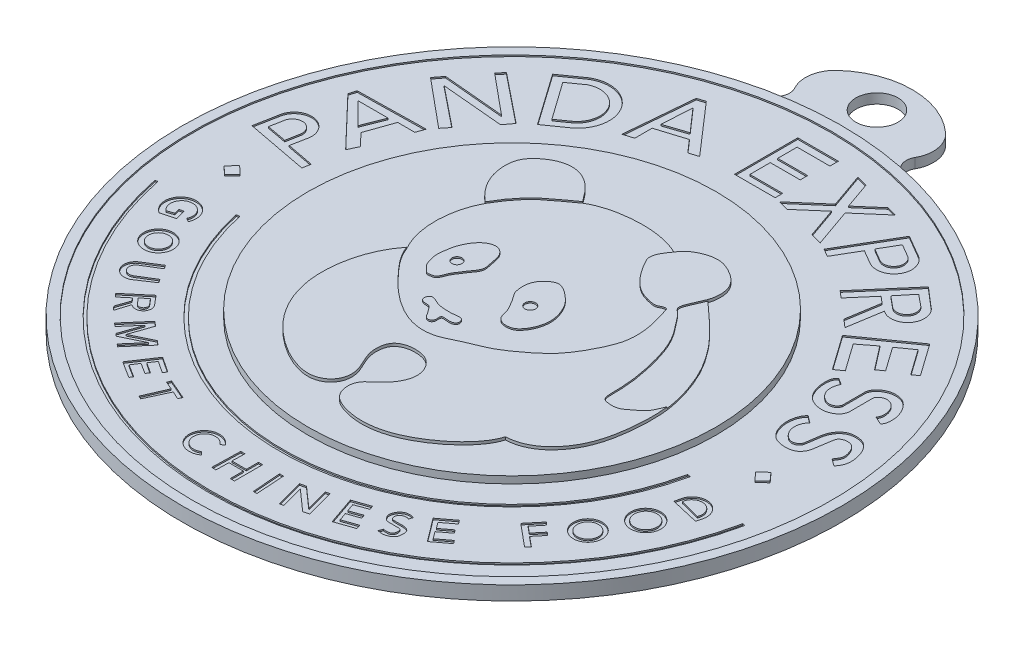
SolidWorks part; units mm, degrees
ref_plane "Front Plane" through (0, 0, 0) normal (0, 0, 1) x (1, 0, 0)
ref_plane "Top Plane" through (0, 0, 0) normal (0, 1, 0) x (1, 0, 0)
ref_plane "Right Plane" through (0, 0, 0) normal (1, 0, 0) x (0, 0, -1)
sketch "Sketch1" plane through (0, 0, 0) normal (0, 1, 0) x (1, 0, 0)
  line L0 (162.6666, 487.9997) -> (813.3328, 487.9997) construction
  line L1 (0, 0) -> (63.5, 0) construction
  line L2 (63.5, 0) -> (63.5, 127) construction
  line L3 (103.964, 54.7894) -> (104.5281, 54.6866)
  line L4 (22.4805, 54.6466) -> (23.0482, 54.7328)
  line L5 (13.9877, 60.9363) -> (15.339, 62.4002)
  line L6 (13.9877, 60.9363) -> (15.402, 59.6308)
  line L7 (15.339, 62.4002) -> (16.7533, 61.0947)
  line L8 (15.402, 59.6308) -> (16.7533, 61.0947)
  line L9 (109.9537, 61.0947) -> (111.4108, 62.4002)
  line L10 (109.9537, 61.0947) -> (111.2682, 59.6276)
  line L11 (111.4108, 62.4002) -> (112.7253, 60.9331)
  line L12 (111.2682, 59.6276) -> (112.7253, 60.9331)
  line L13 (10.7199, 74.026) -> (9.9565, 70.0184)
  line L14 (9.9565, 70.0184) -> (21.0812, 67.8995)
  line L15 (21.0812, 67.8995) -> (21.3558, 69.3411)
  line L16 (21.3558, 69.3411) -> (16.4292, 70.2795)
  line L17 (16.4292, 70.2795) -> (16.918, 72.8454)
  line L18 (11.5977, 71.3543) -> (15.2028, 70.6923)
  line L19 (15.2028, 70.6923) -> (15.638, 73.0619)
  line L20 (11.5977, 71.3543) -> (12.0557, 73.797)
  line L21 (13.9877, 84.9999) -> (13.6218, 83.701)
  line L22 (13.6218, 83.701) -> (22.1944, 74.7201)
  line L23 (22.1944, 74.7201) -> (23.0418, 76.5386)
  line L24 (23.0418, 76.5386) -> (20.8913, 78.7915)
  line L25 (20.8913, 78.7915) -> (22.6181, 83.701)
  line L26 (22.6181, 83.701) -> (25.72, 83.701)
  line L27 (25.72, 83.701) -> (26.2547, 85.2213)
  line L28 (26.2547, 85.2213) -> (13.9877, 84.9999)
  line L29 (15.638, 83.5128) -> (19.5466, 79.6042)
  line L30 (19.5466, 79.6042) -> (21.0812, 83.5128)
  line L31 (21.0812, 83.5128) -> (15.638, 83.5128)
  line L32 (18.5625, 93.6945) -> (19.7288, 95.2416)
  line L33 (19.7288, 95.2416) -> (30.844, 94.2419)
  line L34 (30.844, 94.2419) -> (23.6696, 100.1879)
  line L35 (23.6696, 100.1879) -> (24.635, 101.3527)
  line L36 (24.635, 101.3527) -> (33.4879, 94.2419)
  line L37 (33.4879, 94.2419) -> (32.2791, 92.6385)
  line L38 (32.2791, 92.6385) -> (21.0812, 93.6456)
  line L39 (21.0812, 93.6456) -> (28.3314, 87.8221)
  line L40 (28.3314, 87.8221) -> (27.2568, 86.4843)
  line L41 (27.2568, 86.4843) -> (18.5625, 93.6945)
  line L42 (29.0657, 105.266) -> (35.5853, 96.0134)
  line L43 (35.5853, 96.0134) -> (39.0795, 98.4754)
  line L44 (29.0657, 105.266) -> (32.9708, 108.0177)
  line L45 (31.2718, 104.9038) -> (33.8731, 106.7477)
  line L46 (31.2718, 104.9038) -> (36.0687, 98.1367)
  line L47 (36.0687, 98.1367) -> (38.1393, 99.6045)
  line L48 (44.7439, 102.1174) -> (45.8334, 114.4681)
  line L49 (45.8334, 114.4681) -> (47.2239, 114.9007)
  line L50 (47.2239, 114.9007) -> (55.2583, 105.6612)
  line L51 (55.2583, 105.6612) -> (53.6179, 105.1508)
  line L52 (53.6179, 105.1508) -> (51.6639, 107.3979)
  line L53 (51.6639, 107.3979) -> (46.5286, 105.8003)
  line L54 (46.5286, 105.8003) -> (46.5286, 102.6637)
  line L55 (46.5286, 102.6637) -> (44.7439, 102.1174)
  line L56 (46.7041, 107.1984) -> (47.0631, 112.6468)
  line L57 (47.0631, 112.6468) -> (50.6743, 108.5262)
  line L58 (50.6743, 108.5262) -> (46.7041, 107.1984)
  line L59 (61.1991, 117.4592) -> (61.1991, 106.0361)
  line L60 (61.1991, 106.0361) -> (68.5322, 106.0361)
  line L61 (68.5322, 106.0361) -> (68.5322, 107.3979)
  line L62 (68.5322, 107.3979) -> (62.6014, 107.3979)
  line L63 (62.6014, 107.3979) -> (62.6014, 111.0903)
  line L64 (62.6014, 111.0903) -> (68.0063, 111.0903)
  line L65 (68.0063, 111.0903) -> (68.0063, 112.4342)
  line L66 (68.0063, 112.4342) -> (62.6014, 112.4342)
  line L67 (62.6014, 112.4342) -> (62.6014, 115.9401)
  line L68 (62.6014, 115.9401) -> (68.5322, 115.9401)
  line L69 (68.5322, 115.9401) -> (68.5322, 117.4592)
  line L70 (68.5322, 117.4592) -> (61.1991, 117.4592)
  line L71 (69.5839, 105.8003) -> (74.9887, 110.4768)
  line L72 (74.9887, 110.4768) -> (72.7976, 116.7289)
  line L73 (72.7976, 116.7289) -> (74.7842, 116.203)
  line L74 (74.7842, 116.203) -> (76.4774, 111.3718)
  line L75 (76.4774, 111.3718) -> (80.2912, 114.6716)
  line L76 (80.2912, 114.6716) -> (82.1176, 114.1882)
  line L77 (82.1176, 114.1882) -> (77.2451, 109.9723)
  line L78 (77.2451, 109.9723) -> (79.6813, 103.0209)
  line L79 (79.6813, 103.0209) -> (77.649, 103.5589)
  line L80 (77.649, 103.5589) -> (75.7382, 109.011)
  line L81 (75.7382, 109.011) -> (71.4546, 105.3046)
  line L82 (71.4546, 105.3046) -> (69.5839, 105.8003)
  line L83 (81.0215, 102.4016) -> (86.7023, 112.1353)
  line L84 (86.7023, 112.1353) -> (90.4084, 109.9723)
  line L85 (81.0215, 102.4016) -> (82.4358, 101.5762)
  line L86 (82.4358, 101.5762) -> (84.9011, 105.8003)
  line L87 (84.9011, 105.8003) -> (87.5365, 104.2622)
  line L88 (87.8664, 105.6718) -> (85.5702, 107.0119)
  line L89 (85.5702, 107.0119) -> (87.4135, 110.1702)
  line L90 (87.4135, 110.1702) -> (89.5664, 108.9137)
  line L91 (88.9777, 97.345) -> (96.3498, 105.9267)
  line L92 (96.3498, 105.9267) -> (99.6865, 103.0603)
  line L93 (98.8008, 102.1174) -> (96.6275, 103.9004)
  line L94 (96.6275, 103.9004) -> (94.3513, 101.1258)
  line L95 (94.3513, 101.1258) -> (96.5246, 99.3429)
  line L96 (88.9777, 97.345) -> (90.1972, 96.2974)
  line L97 (90.1972, 96.2974) -> (93.5393, 100.1879)
  line L98 (93.5393, 100.1879) -> (94.7189, 99.1746)
  line L99 (94.7189, 99.1746) -> (93.7575, 93.2389)
  line L100 (93.7575, 93.2389) -> (95.1844, 92.0131)
  line L101 (95.1844, 92.0131) -> (96.1763, 98.1367)
  line L102 (96.1763, 90.5739) -> (105.4166, 97.1166)
  line L103 (105.4166, 97.1166) -> (109.533, 91.3029)
  line L104 (109.533, 91.3029) -> (108.5034, 90.5739)
  line L105 (108.5034, 90.5739) -> (105.2638, 95.1493)
  line L106 (105.2638, 95.1493) -> (102.5657, 93.2389)
  line L107 (102.5657, 93.2389) -> (105.6291, 88.9124)
  line L108 (105.6291, 88.9124) -> (104.462, 88.0861)
  line L109 (104.462, 88.0861) -> (101.2179, 92.2846)
  line L110 (101.2179, 92.2846) -> (98.5011, 90.1854)
  line L111 (98.5011, 90.1854) -> (101.9756, 85.2782)
  line L112 (101.9756, 85.2782) -> (100.6104, 84.3115)
  line L113 (100.6104, 84.3115) -> (96.1763, 90.5739)
  line L114 (107.0927, 83.5128) -> (107.0927, 79.6042)
  line L115 (108.7641, 83.5128) -> (108.7641, 79.3249)
  line L116 (102.5657, 83.5128) -> (103.717, 82.7661)
  line L117 (112.0087, 80.7997) -> (113.5163, 80.1114)
  line L118 (105.6291, 74.8968) -> (106.9577, 73.9007)
  line L119 (114.5794, 70.2795) -> (115.8694, 69.3411)
  line L120 (109.9537, 73.0619) -> (109.533, 70.2795)
  line L121 (111.7035, 72.8454) -> (111.2682, 70.0184)
  line L122 (15.2028, 47.9879) -> (17.7066, 48.6468)
  line L123 (17.7066, 48.6468) -> (17.2211, 50.4918)
  line L124 (17.2211, 50.4918) -> (16.4547, 50.2901)
  line L125 (16.4547, 50.2901) -> (16.7013, 49.3531)
  line L126 (16.7013, 49.3531) -> (15.5006, 48.9396)
  line L127 (18.5625, 49.5938) -> (19.228, 49.2287)
  line L128 (24.0167, 40.3465) -> (24.4231, 39.6835)
  line L129 (24.4231, 39.6835) -> (21.4934, 37.8879)
  line L130 (24.0167, 40.3465) -> (21.0812, 38.4858)
  line L131 (25.72, 37.6403) -> (26.1171, 36.9959)
  line L132 (26.1171, 36.9959) -> (23.167, 35.0292)
  line L133 (25.72, 37.6403) -> (22.7647, 35.8192)
  line L134 (23.8962, 31.4604) -> (27.8482, 34.7839)
  line L135 (27.8482, 34.7839) -> (29.3472, 33.0014)
  line L136 (23.8962, 31.4604) -> (24.4231, 30.834)
  line L137 (24.4231, 30.834) -> (26.1171, 32.2585)
  line L138 (26.1171, 32.2585) -> (26.5527, 31.7406)
  line L139 (26.5527, 31.7406) -> (25.72, 29.2918)
  line L140 (25.72, 29.2918) -> (26.3349, 28.5606)
  line L141 (26.3349, 28.5606) -> (27.1423, 31.1472)
  line L142 (26.6566, 32.7576) -> (27.8482, 33.7683)
  line L143 (27.8482, 33.7683) -> (28.708, 32.7544)
  line L144 (26.6566, 32.7576) -> (27.5164, 31.7438)
  line L145 (28.4348, 26.6918) -> (31.8179, 30.6114)
  line L146 (31.8179, 30.6114) -> (32.6353, 29.9059)
  line L147 (32.6353, 29.9059) -> (31.2718, 25.9615)
  line L148 (31.2718, 25.9615) -> (35.0671, 27.8069)
  line L149 (35.0671, 27.8069) -> (35.8132, 27.163)
  line L150 (35.8132, 27.163) -> (32.4301, 23.2433)
  line L151 (32.4301, 23.2433) -> (31.9535, 23.6547)
  line L152 (31.9535, 23.6547) -> (34.5749, 26.6918)
  line L153 (34.5749, 26.6918) -> (30.6474, 24.7821)
  line L154 (30.6474, 24.7821) -> (30.1942, 25.1732)
  line L155 (30.1942, 25.1732) -> (31.5582, 29.1192)
  line L156 (31.5582, 29.1192) -> (29.024, 26.1832)
  line L157 (29.024, 26.1832) -> (28.4348, 26.6918)
  line L158 (35.2492, 21.358) -> (38.1393, 25.6918)
  line L159 (38.1393, 25.6918) -> (40.9107, 23.8436)
  line L160 (40.9107, 23.8436) -> (40.5104, 23.2433)
  line L161 (40.5104, 23.2433) -> (38.4099, 24.6441)
  line L162 (38.4099, 24.6441) -> (37.5764, 23.3943)
  line L163 (37.5764, 23.3943) -> (39.4556, 22.141)
  line L164 (39.4556, 22.141) -> (39.0795, 21.5473)
  line L165 (39.0795, 21.5473) -> (37.14, 22.776)
  line L166 (37.14, 22.776) -> (36.3016, 21.4526)
  line L167 (36.3016, 21.4526) -> (38.5771, 20.011)
  line L168 (38.5771, 20.011) -> (38.235, 19.4712)
  line L169 (38.235, 19.4712) -> (35.2492, 21.358)
  line L170 (42.6727, 22.776) -> (42.3971, 22.141)
  line L171 (42.3971, 22.141) -> (43.8513, 21.51)
  line L172 (43.8513, 21.51) -> (42.0868, 17.4443)
  line L173 (42.0868, 17.4443) -> (42.6727, 17.1901)
  line L174 (42.6727, 17.1901) -> (44.5352, 21.2131)
  line L175 (44.5352, 21.2131) -> (45.9781, 20.5451)
  line L176 (45.9781, 20.5451) -> (46.2874, 21.2131)
  line L177 (46.2874, 21.2131) -> (42.6727, 22.776)
  line L178 (56.9602, 17.1901) -> (57.5696, 17.5581)
  line L179 (56.4312, 14.4287) -> (56.9602, 13.8997)
  line L180 (59.9452, 18.0048) -> (59.8213, 12.8669)
  line L181 (59.8213, 12.8669) -> (60.5921, 12.8669)
  line L182 (60.5921, 12.8669) -> (60.6475, 15.1642)
  line L183 (60.6475, 15.1642) -> (63.2548, 15.1642)
  line L184 (63.2548, 15.1642) -> (63.2548, 12.8027)
  line L185 (63.2548, 12.8027) -> (64.0049, 12.8027)
  line L186 (64.0049, 12.8027) -> (64.0049, 17.9069)
  line L187 (64.0049, 17.9069) -> (63.2548, 17.9069)
  line L188 (63.2548, 17.9069) -> (63.2548, 15.7077)
  line L189 (63.2548, 15.7077) -> (60.6475, 15.7077)
  line L190 (60.6475, 15.7077) -> (60.7029, 18.0048)
  line L191 (60.7029, 18.0048) -> (59.9452, 18.0048)
  line L192 (66.9633, 18.0048) -> (67.349, 12.8669)
  line L193 (67.349, 12.8669) -> (68.0063, 12.8669)
  line L194 (68.0063, 12.8669) -> (67.6776, 18.0048)
  line L195 (67.6776, 18.0048) -> (66.9633, 18.0048)
  line L196 (70.3286, 18.2694) -> (71.6543, 13.2778)
  line L197 (71.6543, 13.2778) -> (72.3116, 13.4524)
  line L198 (72.3116, 13.4524) -> (71.2429, 17.4761)
  line L199 (71.2429, 17.4761) -> (74.9887, 14.1634)
  line L200 (74.9887, 14.1634) -> (75.9878, 14.4287)
  line L201 (75.9878, 14.4287) -> (74.6486, 19.4712)
  line L202 (74.6486, 19.4712) -> (73.9238, 19.2786)
  line L203 (73.9238, 19.2786) -> (74.9887, 15.2687)
  line L204 (74.9887, 15.2687) -> (71.3482, 18.4883)
  line L205 (71.3482, 18.4883) -> (70.3286, 18.2694)
  line L206 (80.4562, 21.3192) -> (77.4786, 20.2914)
  line L207 (77.4786, 20.2914) -> (79.2123, 15.2687)
  line L208 (79.2123, 15.2687) -> (82.5333, 16.415)
  line L209 (82.5333, 16.415) -> (82.2658, 17.1901)
  line L210 (82.2658, 17.1901) -> (79.6389, 16.2833)
  line L211 (79.6389, 16.2833) -> (79.1405, 17.727)
  line L212 (79.1405, 17.727) -> (81.331, 18.4831)
  line L213 (81.331, 18.4831) -> (81.0971, 19.1609)
  line L214 (81.0971, 19.1609) -> (78.918, 18.3764)
  line L215 (78.918, 18.3764) -> (78.4108, 19.7853)
  line L216 (78.4108, 19.7853) -> (80.7011, 20.6098)
  line L217 (80.7011, 20.6098) -> (80.4562, 21.3192)
  line L218 (84.6608, 21.0412) -> (86.0877, 21.0412)
  line L219 (84.6608, 20.2914) -> (86.2395, 20.2914)
  line L220 (85.937, 23.2433) -> (85.6795, 22.5655)
  line L221 (85.0132, 18.7186) -> (84.786, 18.0048)
  line L222 (87.7863, 24.9363) -> (90.9349, 20.7627)
  line L223 (90.9349, 20.7627) -> (93.6361, 22.8005)
  line L224 (93.6361, 22.8005) -> (93.203, 23.3746)
  line L225 (93.203, 23.3746) -> (91.0172, 21.7256)
  line L226 (91.0172, 21.7256) -> (90.0646, 22.9883)
  line L227 (90.0646, 22.9883) -> (92.0705, 24.5017)
  line L228 (92.0705, 24.5017) -> (91.6207, 25.0979)
  line L229 (91.6207, 25.0979) -> (89.6851, 23.6377)
  line L230 (89.6851, 23.6377) -> (88.8769, 24.7091)
  line L231 (88.8769, 24.7091) -> (91.0057, 26.3151)
  line L232 (91.0057, 26.3151) -> (90.5009, 26.9842)
  line L233 (90.5009, 26.9842) -> (87.7863, 24.9363)
  line L234 (96.5246, 32.0496) -> (100.6011, 28.6689)
  line L235 (100.6011, 28.6689) -> (101.1544, 29.3361)
  line L236 (101.1544, 29.3361) -> (99.377, 30.8101)
  line L237 (99.377, 30.8101) -> (100.8575, 32.5954)
  line L238 (100.8575, 32.5954) -> (100.292, 33.0643)
  line L239 (100.292, 33.0643) -> (98.8293, 31.3005)
  line L240 (98.8293, 31.3005) -> (97.6432, 32.2842)
  line L241 (97.6432, 32.2842) -> (99.1655, 34.1199)
  line L242 (99.1655, 34.1199) -> (98.6212, 34.5713)
  line L243 (96.5246, 32.0496) -> (98.6212, 34.5713)
  line L244 (106.9194, 49.3531) -> (112.0087, 48.1707)
  line L245 (112.0087, 48.1707) -> (112.1874, 48.9396)
  line L246 (106.9194, 49.3531) -> (107.1371, 50.2901)
  line L247 (107.7341, 50.0452) -> (111.4108, 49.1002)
  line L248 (23.0482, 54.7328) -> (9.7293, 52.7088) construction
  line L249 (103.964, 54.7894) -> (117.1147, 51.9585) construction
  line L250 (117.1147, 51.9585) -> (116.6509, 52.0584)
  line L251 (9.7293, 52.7088) -> (10.1988, 52.7802)
  circle A0 centre (63.5, 63.5) radius 59.5857
  circle A1 centre (63.5, 63.5) radius 57.7772
  circle A2 centre (63.5, 63.5) radius 54.8429
  circle A3 centre (63.5, 63.5) radius 54.3685
  arc A4 (22.4805, 54.6466) -> (104.5281, 54.6866) centre (63.5, 63.5) ccw
  arc A5 (23.0482, 54.7328) -> (103.964, 54.7894) centre (63.5, 63.5) ccw
  circle A6 centre (63.5, 63.5) radius 36.8812
  circle A7 centre (51.4141, 65.6307) radius 0.9044
  circle A8 centre (65.1118, 65.1836) radius 0.966
  arc A9 (12.0557, 73.797) -> (15.638, 73.0619) centre (13.8468, 73.4295) cw
  arc A10 (10.7199, 74.026) -> (16.918, 72.8454) centre (13.8738, 73.7239) cw
  arc A11 (33.8731, 106.7477) -> (38.1393, 99.6045) centre (35.7261, 103.0088) cw
  arc A12 (32.9708, 108.0177) -> (39.0795, 98.4754) centre (35.8132, 103.1109) cw
  arc A13 (89.5664, 108.9137) -> (87.8664, 105.6718) centre (88.7164, 107.2927) cw
  arc A14 (90.4084, 109.9723) -> (87.5365, 104.2622) centre (88.9724, 107.1172) cw
  arc A15 (98.8008, 102.1174) -> (96.5246, 99.3429) centre (97.4395, 100.9133) cw
  arc A16 (99.6865, 103.0603) -> (96.1763, 98.1367) centre (97.9314, 100.5985) cw
  arc A17 (107.7341, 50.0452) -> (111.4108, 49.1002) centre (109.6436, 49.8495) cw
  arc A18 (107.1371, 50.2901) -> (112.1874, 48.9396) centre (109.7255, 49.8512) cw
  circle A19 centre (103.717, 36.9959) radius 1.9147
  circle A20 centre (103.717, 36.9959) radius 2.6103
  circle A21 centre (107.3751, 43.8015) radius 2.057
  circle A22 centre (107.3751, 43.8015) radius 2.7122
  arc A23 (56.9602, 17.1901) -> (56.4312, 14.4287) centre (55.315, 16.0739) ccw
  arc A24 (57.5696, 17.5581) -> (56.9602, 13.8997) centre (55.2987, 16.0565) ccw
  arc A25 (21.4934, 37.8879) -> (22.7647, 35.8192) centre (22.1278, 36.8528) ccw
  arc A26 (21.0812, 38.4858) -> (23.167, 35.0292) centre (22.1241, 36.7575) ccw
  circle A27 centre (19.5466, 43.5179) radius 1.8088
  circle A28 centre (19.5466, 43.5179) radius 2.6559
  arc A29 (18.5625, 49.5938) -> (15.5006, 48.9396) centre (16.7672, 50.504) ccw
  arc A30 (19.228, 49.2287) -> (15.2028, 47.9879) centre (16.6593, 50.4124) ccw
  arc A31 (28.708, 32.7544) -> (27.5164, 31.7438) centre (28.1122, 32.2491) cw
  arc A32 (29.3472, 33.0014) -> (27.1423, 31.1472) centre (28.1111, 32.2332) cw
  spline S0 degree 3 poles (106.9577, 73.9007) (106.2669, 73.286) (105.8495, 71.6815) (106.7968, 69.9545) (108.2772, 69.0067) (109.3897, 69.7059) (109.533, 70.2795) knots 0 0 0 0 0.36928 0.573776 0.772986 1 1 1 1
  spline S1 degree 3 poles (109.9537, 73.0619) (110.1155, 73.7978) (110.6088, 74.9337) (112.0099, 75.9412) (113.4245, 76.0572) (114.9755, 75.7494) (116.2003, 74.2917) (116.7308, 72.5184) (116.7568, 70.6688) (116.1661, 69.7507) (115.8694, 69.3411) knots 0 0 0 0 0.168852 0.263752 0.36834 0.476801 0.602253 0.767098 0.885618 1 1 1 1
  spline S2 degree 3 poles (111.7035, 72.8454) (111.7706, 73.2807) (111.8361, 74.0327) (113.1646, 74.5569) (114.5362, 74.1617) (115.1362, 72.8675) (115.4839, 71.4396) (114.8014, 70.655) (114.5794, 70.2795) knots 0 0 0 0 0.141405 0.297656 0.46807 0.645248 0.821101 1 1 1 1
  spline S3 degree 3 poles (105.6291, 74.8968) (104.9921, 74.2526) (104.4941, 72.6932) (104.7773, 70.3681) (105.9806, 68.2312) (108.2392, 67.7858) (110.3675, 68.0828) (111.1493, 69.3175) (111.2682, 70.0184) knots 0 0 0 0 0.203456 0.34811 0.531084 0.712475 0.834522 1 1 1 1
  spline S4 degree 3 poles (103.717, 82.7661) (103.4154, 82.1038) (103.1112, 80.6398) (104.2643, 79.0447) (105.9258, 78.3425) (106.9269, 79.0712) (107.0927, 79.6042) knots 0 0 0 0 0.312222 0.564891 0.770968 1 1 1 1
  spline S5 degree 3 poles (102.5657, 83.5128) (102.0374, 83.0919) (101.8036, 81.8334) (102.0157, 80.2315) (102.5202, 78.8801) (103.4159, 77.7405) (104.7255, 77.1736) (106.1129, 76.9786) (107.7742, 77.4205) (108.7527, 78.3976) (108.7641, 79.3249) knots 0 0 0 0 0.149568 0.279625 0.377893 0.484014 0.608764 0.701019 0.807899 1 1 1 1
  spline S6 degree 3 poles (108.7641, 83.5128) (108.9008, 84.148) (109.944, 84.7473) (111.1534, 84.3521) (111.906, 83.724) (112.4314, 82.4609) (112.4471, 81.4011) (112.0087, 80.7997) knots 0 0 0 0 0.281037 0.409573 0.548465 0.700423 1 1 1 1
  spline S7 degree 3 poles (107.0927, 83.5128) (107.0294, 84.3142) (107.8281, 85.3676) (109.3398, 86.0969) (110.7253, 86.1861) (112.0589, 85.7418) (113.1505, 84.5882) (113.8246, 83.1797) (114.026, 81.5503) (113.8568, 80.5633) (113.5163, 80.1114) knots 0 0 0 0 0.181099 0.287096 0.395438 0.505122 0.611111 0.766301 0.870349 1 1 1 1
  spline S8 degree 3 poles (44.7439, 77.406) (43.8082, 75.6351) (42.4674, 70.8152) (43.2653, 65.7573) (44.7439, 63.187) knots 0 0 0 0 0.406141 1 1 1 1
  spline S9 degree 3 poles (44.7439, 77.406) (43.4227, 78.4867) (41.6812, 80.5555) (40.7331, 84.1031) (40.878, 87.1447) (43.0907, 89.4067) (45.6095, 90.7578) (48.3731, 90.7974) (51.2384, 89.3398) (52.634, 87.4688) (53.5143, 86.2519) knots 0 0 0 0 0.197911 0.294768 0.419538 0.523307 0.641072 0.740777 0.825967 1 1 1 1
  spline S10 degree 3 poles (53.5143, 86.2519) (54.7918, 87.017) (57.4856, 87.943) (63.0659, 88.5621) (67.1967, 87.9985) (69.7343, 86.6984) knots 0 0 0 0 0.265478 0.504085 1 1 1 1
  spline S11 degree 3 poles (69.7343, 86.6984) (70.3602, 87.7677) (72.2174, 89.0163) (75.1925, 89.6204) (77.8797, 88.5367) (80.6735, 86.406) (80.6139, 83.4823) (80.1675, 82.2389) knots 0 0 0 0 0.222957 0.400363 0.53088 0.748916 1 1 1 1
  spline S12 degree 3 poles (80.1675, 82.2389) (81.3273, 81.1524) (83.1319, 79.6408) (85.4152, 77.2665) (87.1337, 75.5414) (88.7353, 73.3752) (90.2149, 71.1459) (91.5753, 68.2462) (92.7631, 64.8963) (93.5758, 60.6813) (93.3983, 55.1326) (92.087, 47.3736) (87.1465, 42.5702) (83.357, 42.4481) knots 0 0 0 0 0.097431 0.143853 0.201819 0.246304 0.30866 0.365412 0.442027 0.526071 0.626468 0.781226 1 1 1 1
  spline S13 degree 3 poles (83.357, 42.4481) (82.8851, 40.8911) (80.8168, 37.9768) (76.7045, 34.7092) (71.2324, 31.9463) (65.8223, 31.6532) (61.8339, 33.4903) (61.0567, 35.6693) (61.2461, 37.762) (62.931, 39.1848) (64.4218, 40.5339) (65.4068, 42.0968) (65.8501, 43.6302) (65.6821, 45.6204) (64.3248, 47.5535) (61.9132, 48.0984) (59.9603, 47.9367) (58.2749, 46.9493) (57.8032, 45.3159) (57.8353, 43.6547) (58.4953, 41.6667) (59.5935, 39.8291) (59.6539, 37.8168) (59.1459, 36.2742) (57.838, 34.9944) (55.7118, 34.3742) (52.234, 35.0276) (48.448, 37.2204) (44.61, 40.7473) (42.1193, 44.807) (40.894, 49.4381) (40.9414, 55.8075) (42.6587, 60.5441) (44.7439, 63.187) knots 0 0 0 0 0.048848 0.105496 0.157748 0.231948 0.263063 0.279858 0.298884 0.322576 0.343013 0.360149 0.377665 0.390165 0.419878 0.440789 0.462196 0.478362 0.496154 0.51023 0.528474 0.558789 0.573415 0.58788 0.606776 0.626174 0.652525 0.711206 0.75609 0.809237 0.85261 0.899288 1 1 1 1
  spline S14 degree 3 poles (48.6703, 65.9436) (49.004, 67.8803) (49.8532, 69.8935) (51.6015, 71.4228) (53.3757, 71.4953) (54.6046, 70.2746) (54.707, 68.5608) (55.2983, 66.9322) (54.5042, 65.6166) (53.7466, 64.6622) (53.1046, 63.6452) (52.609, 62.7721) (52.3134, 61.9339) (51.9682, 61.2453) (51.2156, 61.075) (50.4356, 60.9344) (49.9686, 61.6475) (49.2569, 62.1695) (48.875, 63.2265) (48.518, 64.5697) (48.6703, 65.9436) (49.004, 67.8803) (49.8532, 69.8935) knots -0.155046 -0.10705 -0.039285 0 0.11881 0.204991 0.248621 0.309837 0.378912 0.44414 0.495099 0.543754 0.585908 0.632604 0.65749 0.689786 0.7124 0.744002 0.7697 0.801181 0.844954 0.89295 0.960715 1 1.11881 1.204991 1.248621 only from (48.906, 67.1951) to (48.906, 67.1951)
  spline S15 degree 3 poles (61.3331, 68.2569) (61.8692, 69.6711) (62.8569, 70.6789) (64.1186, 71.3916) (65.4577, 70.8765) (66.7152, 69.9219) (68.0716, 68.648) (68.8746, 66.9682) (69.3424, 65.3189) (69.3019, 63.689) (68.8243, 62.1756) (68.1217, 60.992) (67.2962, 60.1688) (66.2376, 59.8942) (65.134, 59.9399) (64.1302, 60.7168) (63.9813, 61.7488) (63.6623, 62.679) (63.0864, 63.6088) (62.4794, 64.7478) (61.5897, 65.7178) (61.3925, 66.9922) (61.3331, 68.2569) (61.8692, 69.6711) (62.8569, 70.6789) knots -0.127525 -0.095522 -0.047974 0 0.051921 0.09457 0.136057 0.186412 0.256761 0.320847 0.372415 0.429291 0.483087 0.531241 0.568392 0.596925 0.639617 0.676401 0.714269 0.741092 0.776058 0.824275 0.872475 0.904478 0.952026 1 1.051921 1.09457 1.136057 only from (61.9307, 69.5752) to (61.9307, 69.5752)
  spline S16 degree 3 poles (54.1996, 57.0018) (54.3652, 57.5203) (54.9169, 57.8402) (55.5792, 57.5592) (56.2968, 57.2061) (57.2247, 56.9616) (58.3107, 56.9055) (59.3813, 56.897) (60.2521, 57.0792) (60.9745, 57.0072) (61.2322, 56.4923) (61.264, 56.0154) (60.8493, 55.5645) (60.0457, 55.4326) (59.3776, 55.5763) (58.727, 55.5499) (58.6187, 55.1343) (58.6959, 54.7461) (58.6495, 54.2674) (58.2517, 53.7861) (57.3808, 53.9284) (57.0063, 54.777) (56.4588, 55.4151) (56.0636, 56.0519) (55.4123, 56.1334) (54.8579, 56.0989) (54.3081, 56.4218) (54.1996, 57.0018) (54.3652, 57.5203) (54.9169, 57.8402) knots -0.091907 -0.062337 -0.036107 0 0.020638 0.062028 0.107901 0.157293 0.218592 0.289003 0.332184 0.370151 0.395131 0.421086 0.444501 0.489262 0.547033 0.565509 0.584652 0.607134 0.633328 0.661707 0.700084 0.754749 0.804527 0.844681 0.868759 0.908093 0.937663 0.963893 1 1.020638 1.062028 1.107901 only from (54.4794, 57.5483) to (54.4794, 57.5483)
  spline S17 degree 3 poles (44.7439, 63.187) (45.4671, 61.255) (47.6761, 58.7269) (50.8304, 55.4712) (53.9178, 53.1805) (57.299, 51.6491) (61.102, 51.6186) (64.5427, 53.5468) (68.3551, 54.8455) (71.8707, 57.3479) (74.8534, 59.7639) (76.9359, 62.872) (78.271, 65.4707) (79.2929, 68.2071) (79.4656, 71.0689) (78.8932, 74.0574) (78.2583, 75.826) (77.949, 77.1472) (77.371, 77.0737) (76.9493, 76.8948) (76.328, 76.5335) (75.3668, 76.6783) (74.2636, 76.9294) (72.9039, 77.4533) (70.8488, 79.0068) (69.3499, 81.1618) (68.0136, 83.5421) (68.6879, 85.3019) (69.4008, 86.1975) (69.7343, 86.6984) knots 0 0 0 0 0.084514 0.138543 0.188998 0.244098 0.290772 0.341069 0.405874 0.457941 0.519983 0.564584 0.612627 0.641878 0.685531 0.731008 0.76411 0.772247 0.77811 0.784701 0.792201 0.807114 0.822927 0.840088 0.867256 0.928578 0.950665 0.975318 1 1 1 1
  spline S18 degree 3 poles (80.1675, 82.2389) (79.882, 81.6021) (79.4329, 80.4254) (78.798, 79.1552) (78.7087, 77.9891) (79.8844, 77.2329) (80.7376, 75.8834) (82.4251, 73.9296) (83.7589, 71.538) (84.835, 68.2764) (85.6866, 64.801) (86.1335, 61.3521) (86.0947, 58.9597) (86.1706, 57.7864) (86.5893, 57.1268) (87.6498, 56.9429) (89.1821, 56.8989) (90.6276, 58.1495) (92.4605, 59.3875) (92.918, 60.9664) (93.2943, 61.7661) knots 0 0 0 0 0.057767 0.103672 0.117957 0.148669 0.205072 0.25332 0.360504 0.428908 0.536815 0.656119 0.714717 0.73487 0.75272 0.773985 0.819419 0.875141 0.924624 1 1 1 1
  spline S19 degree 3 poles (44.7439, 77.406) (45.85, 79.3716) (48.3765, 82.8545) (52.0077, 85.0626) (53.5143, 86.2519) knots 0 0 0 0 0.540843 1 1 1 1
  spline S20 degree 3 poles (86.0877, 21.0412) (86.3064, 21.0412) (86.8095, 21.0176) (87.5769, 20.55) (87.5703, 19.5854) (87.4259, 18.6156) (86.3456, 17.8761) (85.4044, 17.8264) (84.786, 18.0048) knots 0 0 0 0 0.123616 0.223801 0.413052 0.540297 0.695435 1 1 1 1
  spline S21 degree 3 poles (86.2395, 20.2914) (86.5402, 20.2972) (86.7669, 19.8249) (86.6881, 19.1657) (86.0773, 18.5605) (85.4005, 18.6779) (85.0132, 18.7186) knots 0 0 0 0 0.236795 0.438211 0.605222 1 1 1 1
  spline S22 degree 3 poles (85.6795, 22.5655) (85.4428, 22.7282) (84.9668, 22.6844) (84.315, 22.436) (83.9155, 21.6963) (84.146, 21.0144) (84.6608, 21.0412) knots 0 0 0 0 0.25547 0.441262 0.642293 1 1 1 1
  spline S23 degree 3 poles (85.937, 23.2433) (85.4986, 23.3968) (84.7487, 23.4765) (83.8876, 23.0073) (83.4638, 22.4552) (83.2477, 21.8679) (83.2116, 21.2984) (83.5058, 20.7889) (83.9717, 20.2895) (84.4061, 20.2914) (84.6608, 20.2914) knots 0 0 0 0 0.242329 0.357848 0.489153 0.589484 0.677824 0.769676 0.886414 1 1 1 1
  dimension "D1" = 63.5
  dimension "D2" = 127
sketch "Sketch2" plane through (0, 0, 0) normal (0, 1, 0) x (1, 0, 0)
  circle A0 centre (63.5, 63.5) radius 59.5857 construction
  circle A1 centre (63.5, 63.5) radius 59.5857
extrude "Boss-Extrude1" add sketch "Sketch2" along normal blind 2.54
sketch "Sketch3" plane through (0, 2.54, 0) normal (0, 1, 0) x (1, 0, 0)
  circle A0 centre (63.5, 63.5) radius 57.7772 construction
  circle A1 centre (63.5, 63.5) radius 57.7772
extrude "Cut-Extrude1" cut sketch "Sketch3" against normal blind 0.254
sketch "Sketch4" plane through (0, 2.286, 0) normal (0, 1, 0) x (1, 0, 0)
  line L0 (103.964, 54.7894) -> (104.5281, 54.6866) construction
  line L1 (22.4805, 54.6466) -> (23.0482, 54.7328) construction
  line L2 (103.964, 54.7894) -> (104.5281, 54.6866)
  line L3 (22.4805, 54.6466) -> (23.0482, 54.7328)
  line L4 (117.1147, 51.9585) -> (116.6509, 52.0584) construction
  line L5 (9.7293, 52.7088) -> (10.1988, 52.7802) construction
  line L6 (117.1147, 51.9585) -> (116.6509, 52.0584)
  line L7 (9.7293, 52.7088) -> (10.1988, 52.7802)
  arc A0 (23.0482, 54.7328) -> (103.964, 54.7894) centre (63.5, 63.5) ccw construction
  arc A1 (22.4805, 54.6466) -> (104.5281, 54.6866) centre (63.5, 63.5) ccw construction
  circle A2 centre (63.5, 63.5) radius 54.3685 construction
  circle A3 centre (63.5, 63.5) radius 54.8429 construction
  arc A4 (23.0482, 54.7328) -> (103.964, 54.7894) centre (63.5, 63.5) ccw
  arc A5 (22.4805, 54.6466) -> (104.5281, 54.6866) centre (63.5, 63.5) ccw
  circle A6 centre (63.5, 63.5) radius 54.3685
  circle A7 centre (63.5, 63.5) radius 54.8429
extrude "Cut-Extrude2" cut sketch "Sketch4" against normal blind 0.254 contours L7 A7 L6 A6 | A4 L2 A5 L3 region at (63.1176, 2.286, -8.7746)
sketch "Sketch5" plane through (0, 2.286, 0) normal (0, 1, 0) x (1, 0, 0)
  circle A0 centre (63.5, 63.5) radius 36.8812 construction
  circle A1 centre (63.5, 63.5) radius 36.8812
extrude "Boss-Extrude2" add sketch "Sketch5" along normal blind 1.27
sketch "Sketch6" plane through (0, 2.286, 0) normal (0, 1, 0) x (1, 0, 0)
  line L0 (47.2239, 114.9007) -> (55.2583, 105.6612) construction
  line L1 (53.6179, 105.1508) -> (51.6639, 107.3979) construction
  line L2 (55.2583, 105.6612) -> (53.6179, 105.1508) construction
  line L3 (46.5286, 102.6637) -> (44.7439, 102.1174) construction
  line L4 (46.5286, 105.8003) -> (46.5286, 102.6637) construction
  line L5 (51.6639, 107.3979) -> (46.5286, 105.8003) construction
  line L6 (50.6743, 108.5262) -> (46.7041, 107.1984) construction
  line L7 (46.7041, 107.1984) -> (47.0631, 112.6468) construction
  line L8 (47.0631, 112.6468) -> (50.6743, 108.5262) construction
  line L9 (44.7439, 102.1174) -> (45.8334, 114.4681) construction
  line L10 (45.8334, 114.4681) -> (47.2239, 114.9007) construction
  line L11 (36.0687, 98.1367) -> (38.1393, 99.6045) construction
  line L12 (35.5853, 96.0134) -> (39.0795, 98.4754) construction
  line L13 (29.0657, 105.266) -> (35.5853, 96.0134) construction
  line L14 (31.2718, 104.9038) -> (36.0687, 98.1367) construction
  line L15 (29.0657, 105.266) -> (32.9708, 108.0177) construction
  line L16 (31.2718, 104.9038) -> (33.8731, 106.7477) construction
  line L17 (33.4879, 94.2419) -> (32.2791, 92.6385) construction
  line L18 (28.3314, 87.8221) -> (27.2568, 86.4843) construction
  line L19 (27.2568, 86.4843) -> (18.5625, 93.6945) construction
  line L20 (21.0812, 93.6456) -> (28.3314, 87.8221) construction
  line L21 (32.2791, 92.6385) -> (21.0812, 93.6456) construction
  line L22 (19.7288, 95.2416) -> (30.844, 94.2419) construction
  line L23 (30.844, 94.2419) -> (23.6696, 100.1879) construction
  line L24 (24.635, 101.3527) -> (33.4879, 94.2419) construction
  line L25 (23.6696, 100.1879) -> (24.635, 101.3527) construction
  line L26 (18.5625, 93.6945) -> (19.7288, 95.2416) construction
  line L27 (23.0418, 76.5386) -> (20.8913, 78.7915) construction
  line L28 (22.1944, 74.7201) -> (23.0418, 76.5386) construction
  line L29 (13.9877, 84.9999) -> (13.6218, 83.701) construction
  line L30 (25.72, 83.701) -> (26.2547, 85.2213) construction
  line L31 (26.2547, 85.2213) -> (13.9877, 84.9999) construction
  line L32 (22.6181, 83.701) -> (25.72, 83.701) construction
  line L33 (20.8913, 78.7915) -> (22.6181, 83.701) construction
  line L34 (19.5466, 79.6042) -> (21.0812, 83.5128) construction
  line L35 (15.638, 83.5128) -> (19.5466, 79.6042) construction
  line L36 (21.0812, 83.5128) -> (15.638, 83.5128) construction
  line L37 (9.9565, 70.0184) -> (21.0812, 67.8995) construction
  line L38 (21.0812, 67.8995) -> (21.3558, 69.3411) construction
  line L39 (21.3558, 69.3411) -> (16.4292, 70.2795) construction
  line L40 (16.4292, 70.2795) -> (16.918, 72.8454) construction
  line L41 (15.2028, 70.6923) -> (15.638, 73.0619) construction
  line L42 (11.5977, 71.3543) -> (15.2028, 70.6923) construction
  line L43 (11.5977, 71.3543) -> (12.0557, 73.797) construction
  line L44 (10.7199, 74.026) -> (9.9565, 70.0184) construction
  line L45 (13.6218, 83.701) -> (22.1944, 74.7201) construction
  line L46 (47.2239, 114.9007) -> (55.2583, 105.6612)
  line L47 (53.6179, 105.1508) -> (51.6639, 107.3979)
  line L48 (55.2583, 105.6612) -> (53.6179, 105.1508)
  line L49 (46.5286, 102.6637) -> (44.7439, 102.1174)
  line L50 (46.5286, 105.8003) -> (46.5286, 102.6637)
  line L51 (51.6639, 107.3979) -> (46.5286, 105.8003)
  line L52 (50.6743, 108.5262) -> (46.7041, 107.1984)
  line L53 (46.7041, 107.1984) -> (47.0631, 112.6468)
  line L54 (47.0631, 112.6468) -> (50.6743, 108.5262)
  line L55 (44.7439, 102.1174) -> (45.8334, 114.4681)
  line L56 (45.8334, 114.4681) -> (47.2239, 114.9007)
  line L57 (36.0687, 98.1367) -> (38.1393, 99.6045)
  line L58 (35.5853, 96.0134) -> (39.0795, 98.4754)
  line L59 (29.0657, 105.266) -> (35.5853, 96.0134)
  line L60 (31.2718, 104.9038) -> (36.0687, 98.1367)
  line L61 (29.0657, 105.266) -> (32.9708, 108.0177)
  line L62 (31.2718, 104.9038) -> (33.8731, 106.7477)
  line L63 (33.4879, 94.2419) -> (32.2791, 92.6385)
  line L64 (28.3314, 87.8221) -> (27.2568, 86.4843)
  line L65 (27.2568, 86.4843) -> (18.5625, 93.6945)
  line L66 (21.0812, 93.6456) -> (28.3314, 87.8221)
  line L67 (32.2791, 92.6385) -> (21.0812, 93.6456)
  line L68 (19.7288, 95.2416) -> (30.844, 94.2419)
  line L69 (30.844, 94.2419) -> (23.6696, 100.1879)
  line L70 (24.635, 101.3527) -> (33.4879, 94.2419)
  line L71 (23.6696, 100.1879) -> (24.635, 101.3527)
  line L72 (18.5625, 93.6945) -> (19.7288, 95.2416)
  line L73 (23.0418, 76.5386) -> (20.8913, 78.7915)
  line L74 (22.1944, 74.7201) -> (23.0418, 76.5386)
  line L75 (13.9877, 84.9999) -> (13.6218, 83.701)
  line L76 (25.72, 83.701) -> (26.2547, 85.2213)
  line L77 (26.2547, 85.2213) -> (13.9877, 84.9999)
  line L78 (22.6181, 83.701) -> (25.72, 83.701)
  line L79 (20.8913, 78.7915) -> (22.6181, 83.701)
  line L80 (19.5466, 79.6042) -> (21.0812, 83.5128)
  line L81 (15.638, 83.5128) -> (19.5466, 79.6042)
  line L82 (21.0812, 83.5128) -> (15.638, 83.5128)
  line L83 (9.9565, 70.0184) -> (21.0812, 67.8995)
  line L84 (21.0812, 67.8995) -> (21.3558, 69.3411)
  line L85 (21.3558, 69.3411) -> (16.4292, 70.2795)
  line L86 (16.4292, 70.2795) -> (16.918, 72.8454)
  line L87 (15.2028, 70.6923) -> (15.638, 73.0619)
  line L88 (11.5977, 71.3543) -> (15.2028, 70.6923)
  line L89 (11.5977, 71.3543) -> (12.0557, 73.797)
  line L90 (10.7199, 74.026) -> (9.9565, 70.0184)
  line L91 (13.6218, 83.701) -> (22.1944, 74.7201)
  line L92 (114.5794, 70.2795) -> (115.8694, 69.3411) construction
  line L93 (111.7035, 72.8454) -> (111.2682, 70.0184) construction
  line L94 (109.9537, 73.0619) -> (109.533, 70.2795) construction
  line L95 (105.6291, 74.8968) -> (106.9577, 73.9007) construction
  line L96 (102.5657, 83.5128) -> (103.717, 82.7661) construction
  line L97 (108.7641, 83.5128) -> (108.7641, 79.3249) construction
  line L98 (107.0927, 83.5128) -> (107.0927, 79.6042) construction
  line L99 (112.0087, 80.7997) -> (113.5163, 80.1114) construction
  line L100 (108.5034, 90.5739) -> (105.2638, 95.1493) construction
  line L101 (105.6291, 88.9124) -> (104.462, 88.0861) construction
  line L102 (101.9756, 85.2782) -> (100.6104, 84.3115) construction
  line L103 (100.6104, 84.3115) -> (96.1763, 90.5739) construction
  line L104 (109.533, 91.3029) -> (108.5034, 90.5739) construction
  line L105 (105.4166, 97.1166) -> (109.533, 91.3029) construction
  line L106 (105.2638, 95.1493) -> (102.5657, 93.2389) construction
  line L107 (102.5657, 93.2389) -> (105.6291, 88.9124) construction
  line L108 (104.462, 88.0861) -> (101.2179, 92.2846) construction
  line L109 (101.2179, 92.2846) -> (98.5011, 90.1854) construction
  line L110 (98.5011, 90.1854) -> (101.9756, 85.2782) construction
  line L111 (96.1763, 90.5739) -> (105.4166, 97.1166) construction
  line L112 (93.7575, 93.2389) -> (95.1844, 92.0131) construction
  line L113 (98.8008, 102.1174) -> (96.6275, 103.9004) construction
  line L114 (96.3498, 105.9267) -> (99.6865, 103.0603) construction
  line L115 (95.1844, 92.0131) -> (96.1763, 98.1367) construction
  line L116 (94.7189, 99.1746) -> (93.7575, 93.2389) construction
  line L117 (88.9777, 97.345) -> (90.1972, 96.2974) construction
  line L118 (90.1972, 96.2974) -> (93.5393, 100.1879) construction
  line L119 (93.5393, 100.1879) -> (94.7189, 99.1746) construction
  line L120 (94.3513, 101.1258) -> (96.5246, 99.3429) construction
  line L121 (96.6275, 103.9004) -> (94.3513, 101.1258) construction
  line L122 (88.9777, 97.345) -> (96.3498, 105.9267) construction
  line L123 (87.8664, 105.6718) -> (85.5702, 107.0119) construction
  line L124 (84.9011, 105.8003) -> (87.5365, 104.2622) construction
  line L125 (82.4358, 101.5762) -> (84.9011, 105.8003) construction
  line L126 (81.0215, 102.4016) -> (82.4358, 101.5762) construction
  line L127 (81.0215, 102.4016) -> (86.7023, 112.1353) construction
  line L128 (85.5702, 107.0119) -> (87.4135, 110.1702) construction
  line L129 (87.4135, 110.1702) -> (89.5664, 108.9137) construction
  line L130 (86.7023, 112.1353) -> (90.4084, 109.9723) construction
  line L131 (71.4546, 105.3046) -> (69.5839, 105.8003) construction
  line L132 (69.5839, 105.8003) -> (74.9887, 110.4768) construction
  line L133 (75.7382, 109.011) -> (71.4546, 105.3046) construction
  line L134 (77.649, 103.5589) -> (75.7382, 109.011) construction
  line L135 (79.6813, 103.0209) -> (77.649, 103.5589) construction
  line L136 (77.2451, 109.9723) -> (79.6813, 103.0209) construction
  line L137 (82.1176, 114.1882) -> (77.2451, 109.9723) construction
  line L138 (80.2912, 114.6716) -> (82.1176, 114.1882) construction
  line L139 (76.4774, 111.3718) -> (80.2912, 114.6716) construction
  line L140 (74.7842, 116.203) -> (76.4774, 111.3718) construction
  line L141 (72.7976, 116.7289) -> (74.7842, 116.203) construction
  line L142 (74.9887, 110.4768) -> (72.7976, 116.7289) construction
  line L143 (68.0063, 111.0903) -> (68.0063, 112.4342) construction
  line L144 (61.1991, 106.0361) -> (68.5322, 106.0361) construction
  line L145 (68.5322, 106.0361) -> (68.5322, 107.3979) construction
  line L146 (68.5322, 107.3979) -> (62.6014, 107.3979) construction
  line L147 (62.6014, 107.3979) -> (62.6014, 111.0903) construction
  line L148 (62.6014, 111.0903) -> (68.0063, 111.0903) construction
  line L149 (68.0063, 112.4342) -> (62.6014, 112.4342) construction
  line L150 (61.1991, 117.4592) -> (61.1991, 106.0361) construction
  line L151 (62.6014, 112.4342) -> (62.6014, 115.9401) construction
  line L152 (62.6014, 115.9401) -> (68.5322, 115.9401) construction
  line L153 (68.5322, 115.9401) -> (68.5322, 117.4592) construction
  line L154 (68.5322, 117.4592) -> (61.1991, 117.4592) construction
  line L155 (114.5794, 70.2795) -> (115.8694, 69.3411)
  line L156 (111.7035, 72.8454) -> (111.2682, 70.0184)
  line L157 (109.9537, 73.0619) -> (109.533, 70.2795)
  line L158 (105.6291, 74.8968) -> (106.9577, 73.9007)
  line L159 (102.5657, 83.5128) -> (103.717, 82.7661)
  line L160 (108.7641, 83.5128) -> (108.7641, 79.3249)
  line L161 (107.0927, 83.5128) -> (107.0927, 79.6042)
  line L162 (112.0087, 80.7997) -> (113.5163, 80.1114)
  line L163 (108.5034, 90.5739) -> (105.2638, 95.1493)
  line L164 (105.6291, 88.9124) -> (104.462, 88.0861)
  line L165 (101.9756, 85.2782) -> (100.6104, 84.3115)
  line L166 (100.6104, 84.3115) -> (96.1763, 90.5739)
  line L167 (109.533, 91.3029) -> (108.5034, 90.5739)
  line L168 (105.4166, 97.1166) -> (109.533, 91.3029)
  line L169 (105.2638, 95.1493) -> (102.5657, 93.2389)
  line L170 (102.5657, 93.2389) -> (105.6291, 88.9124)
  line L171 (104.462, 88.0861) -> (101.2179, 92.2846)
  line L172 (101.2179, 92.2846) -> (98.5011, 90.1854)
  line L173 (98.5011, 90.1854) -> (101.9756, 85.2782)
  line L174 (96.1763, 90.5739) -> (105.4166, 97.1166)
  line L175 (93.7575, 93.2389) -> (95.1844, 92.0131)
  line L176 (98.8008, 102.1174) -> (96.6275, 103.9004)
  line L177 (96.3498, 105.9267) -> (99.6865, 103.0603)
  line L178 (95.1844, 92.0131) -> (96.1763, 98.1367)
  line L179 (94.7189, 99.1746) -> (93.7575, 93.2389)
  line L180 (88.9777, 97.345) -> (90.1972, 96.2974)
  line L181 (90.1972, 96.2974) -> (93.5393, 100.1879)
  line L182 (93.5393, 100.1879) -> (94.7189, 99.1746)
  line L183 (94.3513, 101.1258) -> (96.5246, 99.3429)
  line L184 (96.6275, 103.9004) -> (94.3513, 101.1258)
  line L185 (88.9777, 97.345) -> (96.3498, 105.9267)
  line L186 (87.8664, 105.6718) -> (85.5702, 107.0119)
  line L187 (84.9011, 105.8003) -> (87.5365, 104.2622)
  line L188 (82.4358, 101.5762) -> (84.9011, 105.8003)
  line L189 (81.0215, 102.4016) -> (82.4358, 101.5762)
  line L190 (81.0215, 102.4016) -> (86.7023, 112.1353)
  line L191 (85.5702, 107.0119) -> (87.4135, 110.1702)
  line L192 (87.4135, 110.1702) -> (89.5664, 108.9137)
  line L193 (86.7023, 112.1353) -> (90.4084, 109.9723)
  line L194 (71.4546, 105.3046) -> (69.5839, 105.8003)
  line L195 (69.5839, 105.8003) -> (74.9887, 110.4768)
  line L196 (75.7382, 109.011) -> (71.4546, 105.3046)
  line L197 (77.649, 103.5589) -> (75.7382, 109.011)
  line L198 (79.6813, 103.0209) -> (77.649, 103.5589)
  line L199 (77.2451, 109.9723) -> (79.6813, 103.0209)
  line L200 (82.1176, 114.1882) -> (77.2451, 109.9723)
  line L201 (80.2912, 114.6716) -> (82.1176, 114.1882)
  line L202 (76.4774, 111.3718) -> (80.2912, 114.6716)
  line L203 (74.7842, 116.203) -> (76.4774, 111.3718)
  line L204 (72.7976, 116.7289) -> (74.7842, 116.203)
  line L205 (74.9887, 110.4768) -> (72.7976, 116.7289)
  line L206 (68.0063, 111.0903) -> (68.0063, 112.4342)
  line L207 (61.1991, 106.0361) -> (68.5322, 106.0361)
  line L208 (68.5322, 106.0361) -> (68.5322, 107.3979)
  line L209 (68.5322, 107.3979) -> (62.6014, 107.3979)
  line L210 (62.6014, 107.3979) -> (62.6014, 111.0903)
  line L211 (62.6014, 111.0903) -> (68.0063, 111.0903)
  line L212 (68.0063, 112.4342) -> (62.6014, 112.4342)
  line L213 (61.1991, 117.4592) -> (61.1991, 106.0361)
  line L214 (62.6014, 112.4342) -> (62.6014, 115.9401)
  line L215 (62.6014, 115.9401) -> (68.5322, 115.9401)
  line L216 (68.5322, 115.9401) -> (68.5322, 117.4592)
  line L217 (68.5322, 117.4592) -> (61.1991, 117.4592)
  arc A0 (38.1393, 99.6045) -> (33.8731, 106.7477) centre (35.7261, 103.0088) ccw construction
  arc A1 (39.0795, 98.4754) -> (32.9708, 108.0177) centre (35.8132, 103.1109) ccw construction
  arc A2 (15.638, 73.0619) -> (12.0557, 73.797) centre (13.8468, 73.4295) ccw construction
  arc A3 (16.918, 72.8454) -> (10.7199, 74.026) centre (13.8738, 73.7239) ccw construction
  arc A4 (38.1393, 99.6045) -> (33.8731, 106.7477) centre (35.7261, 103.0088) ccw
  arc A5 (39.0795, 98.4754) -> (32.9708, 108.0177) centre (35.8132, 103.1109) ccw
  arc A6 (15.638, 73.0619) -> (12.0557, 73.797) centre (13.8468, 73.4295) ccw
  arc A7 (16.918, 72.8454) -> (10.7199, 74.026) centre (13.8738, 73.7239) ccw
  arc A8 (96.5246, 99.3429) -> (98.8008, 102.1174) centre (97.4395, 100.9133) ccw construction
  arc A9 (96.1763, 98.1367) -> (99.6865, 103.0603) centre (97.9314, 100.5985) ccw construction
  arc A10 (87.5365, 104.2622) -> (90.4084, 109.9723) centre (88.9724, 107.1172) ccw construction
  arc A11 (87.8664, 105.6718) -> (89.5664, 108.9137) centre (88.7164, 107.2927) ccw construction
  arc A12 (96.5246, 99.3429) -> (98.8008, 102.1174) centre (97.4395, 100.9133) ccw
  arc A13 (96.1763, 98.1367) -> (99.6865, 103.0603) centre (97.9314, 100.5985) ccw
  arc A14 (87.5365, 104.2622) -> (90.4084, 109.9723) centre (88.9724, 107.1172) ccw
  arc A15 (87.8664, 105.6718) -> (89.5664, 108.9137) centre (88.7164, 107.2927) ccw
  spline S0 degree 3 poles (-338.3941, 2021.5116) (207.9819, -51.3988) (95.7056, 64.2164) (112.0099, 75.9412) (113.4245, 76.0572) (114.9755, 75.7494) (116.2003, 74.2917) (116.7308, 72.5184) (116.9394, 57.6818) (14.8657, 71.4344) (2114.6625, 137.1073) knots -3.918018 -3.918018 -3.918018 -3.918018 0.168852 0.263752 0.36834 0.476801 0.602253 0.767098 0.885618 3.792837 3.792837 3.792837 3.792837 only from (109.9537, 73.0619) to (115.8694, 69.3411) construction
  spline S1 degree 3 poles (-1887.6336, 94.2981) (187.6764, 16.8264) (103.4268, 70.7143) (113.1646, 74.5569) (114.5362, 74.1617) (115.1362, 72.8675) (117.5289, 63.0424) (31.6676, 69.8578) (2110.7934, -51.1415) knots -2.962851 -2.962851 -2.962851 -2.962851 0.141405 0.297656 0.46807 0.645248 0.821101 4.128146 4.128146 4.128146 4.128146 only from (111.7035, 72.8454) to (114.5794, 70.2795) construction
  spline S2 degree 3 poles (1078.4522, -1671.0185) (187.858, 110.1411) (102.5811, 88.3994) (104.7773, 70.3681) (105.9806, 68.2312) (108.2392, 67.7858) (123.0718, 69.8558) (76.78, 193.1008) (-929.4245, -1636.3427) knots -3.587445 -3.587445 -3.587445 -3.587445 0.203456 0.34811 0.531084 0.712475 0.834522 3.79902 3.79902 3.79902 3.79902 only from (105.6291, 74.8968) to (111.2682, 70.0184) construction
  spline S3 degree 3 poles (277.3577, -1916.9775) (214.2909, 132.4463) (99.2026, 83.7993) (106.7968, 69.9545) (116.3102, 63.8637) (134.4755, 167.3132) (-1837.966, -379.7403) knots -5.423863 -5.423863 -5.423863 -5.423863 0.36928 0.573776 0.772986 4.422331 4.422331 4.422331 4.422331 only from (106.9577, 73.9007) to (109.533, 70.2795) construction
  spline S4 degree 3 poles (-1103.4467, -1511.0889) (228.6858, 142.5053) (94.5108, 92.537) (104.2643, 79.0447) (115.125, 74.4546) (120.6192, 181.6625) (-1780.7204, -576.7516) knots -5.750423 -5.750423 -5.750423 -5.750423 0.312222 0.564891 0.770968 4.807937 4.807937 4.807937 4.807937 only from (103.717, 82.7661) to (107.0927, 79.6042) construction
  spline S5 degree 3 poles (1629.9858, -1207.04) (134.6215, 109.9786) (100.4614, 91.9729) (102.0157, 80.2315) (102.5202, 78.8801) (103.4159, 77.7405) (104.7255, 77.1736) (106.1129, 76.9786) (119.7439, 80.6043) (101.3311, 153.6604) (-1860.0602, 425.8853) knots -2.392022 -2.392022 -2.392022 -2.392022 0.149568 0.279625 0.377893 0.484014 0.608764 0.701019 0.807899 3.818902 3.818902 3.818902 3.818902 only from (102.5657, 83.5128) to (108.7641, 79.3249) construction
  spline S6 degree 3 poles (2076.3878, 435.776) (76.9942, -5.8036) (101.4725, 87.516) (111.1534, 84.3521) (111.906, 83.724) (117.0158, 71.4406) (62.5344, 44.9927) (-1726.2528, 867.5062) knots -3.842001 -3.842001 -3.842001 -3.842001 0.281037 0.409573 0.548465 0.700423 6.151694 6.151694 6.151694 6.151694 only from (108.7641, 83.5128) to (112.0087, 80.7997) construction
  spline S7 degree 3 poles (2102.5516, 205.6338) (119.3609, 15.4262) (97.257, 80.2671) (109.3398, 86.0969) (110.7253, 86.1861) (112.0589, 85.7418) (113.1505, 84.5882) (113.8246, 83.1797) (115.4196, 70.2762) (71.4892, 56.7888) (-1633.2478, 1053.437) knots -2.765266 -2.765266 -2.765266 -2.765266 0.181099 0.287096 0.395438 0.505122 0.611111 0.766301 0.870349 3.690812 3.690812 3.690812 3.690812 only from (107.0927, 83.5128) to (113.5163, 80.1114) construction
  spline S8 degree 3 poles (109.9537, 73.0619) (110.1155, 73.7978) (110.6088, 74.9337) (112.0099, 75.9412) (113.4245, 76.0572) (114.9755, 75.7494) (116.2003, 74.2917) (116.7308, 72.5184) (116.7568, 70.6688) (116.1661, 69.7507) (115.8694, 69.3411) knots 0 0 0 0 0.168852 0.263752 0.36834 0.476801 0.602253 0.767098 0.885618 1 1 1 1
  spline S9 degree 3 poles (111.7035, 72.8454) (111.7706, 73.2807) (111.8361, 74.0327) (113.1646, 74.5569) (114.5362, 74.1617) (115.1362, 72.8675) (115.4839, 71.4396) (114.8014, 70.655) (114.5794, 70.2795) knots 0 0 0 0 0.141405 0.297656 0.46807 0.645248 0.821101 1 1 1 1
  spline S10 degree 3 poles (105.6291, 74.8968) (104.9921, 74.2526) (104.4941, 72.6932) (104.7773, 70.3681) (105.9806, 68.2312) (108.2392, 67.7858) (110.3675, 68.0828) (111.1493, 69.3175) (111.2682, 70.0184) knots 0 0 0 0 0.203456 0.34811 0.531084 0.712475 0.834522 1 1 1 1
  spline S11 degree 3 poles (106.9577, 73.9007) (106.2669, 73.286) (105.8495, 71.6815) (106.7968, 69.9545) (108.2772, 69.0067) (109.3897, 69.7059) (109.533, 70.2795) knots 0 0 0 0 0.36928 0.573776 0.772986 1 1 1 1
  spline S12 degree 3 poles (103.717, 82.7661) (103.4154, 82.1038) (103.1112, 80.6398) (104.2643, 79.0447) (105.9258, 78.3425) (106.9269, 79.0712) (107.0927, 79.6042) knots 0 0 0 0 0.312222 0.564891 0.770968 1 1 1 1
  spline S13 degree 3 poles (102.5657, 83.5128) (102.0374, 83.0919) (101.8036, 81.8334) (102.0157, 80.2315) (102.5202, 78.8801) (103.4159, 77.7405) (104.7255, 77.1736) (106.1129, 76.9786) (107.7742, 77.4205) (108.7527, 78.3976) (108.7641, 79.3249) knots 0 0 0 0 0.149568 0.279625 0.377893 0.484014 0.608764 0.701019 0.807899 1 1 1 1
  spline S14 degree 3 poles (108.7641, 83.5128) (108.9008, 84.148) (109.944, 84.7473) (111.1534, 84.3521) (111.906, 83.724) (112.4314, 82.4609) (112.4471, 81.4011) (112.0087, 80.7997) knots 0 0 0 0 0.281037 0.409573 0.548465 0.700423 1 1 1 1
  spline S15 degree 3 poles (107.0927, 83.5128) (107.0294, 84.3142) (107.8281, 85.3676) (109.3398, 86.0969) (110.7253, 86.1861) (112.0589, 85.7418) (113.1505, 84.5882) (113.8246, 83.1797) (114.026, 81.5503) (113.8568, 80.5633) (113.5163, 80.1114) knots 0 0 0 0 0.181099 0.287096 0.395438 0.505122 0.611111 0.766301 0.870349 1 1 1 1
extrude "Cut-Extrude3" cut sketch "Sketch6" against normal blind 0.254
sketch "Sketch7" plane through (0, 2.286, 0) normal (0, 1, 0) x (1, 0, 0)
  line L0 (109.9537, 61.0947) -> (111.2682, 59.6276) construction
  line L1 (111.2682, 59.6276) -> (112.7253, 60.9331) construction
  line L2 (111.4108, 62.4002) -> (112.7253, 60.9331) construction
  line L3 (109.9537, 61.0947) -> (111.4108, 62.4002) construction
  line L4 (13.9877, 60.9363) -> (15.402, 59.6308) construction
  line L5 (15.402, 59.6308) -> (16.7533, 61.0947) construction
  line L6 (15.339, 62.4002) -> (16.7533, 61.0947) construction
  line L7 (13.9877, 60.9363) -> (15.339, 62.4002) construction
  line L8 (109.9537, 61.0947) -> (111.2682, 59.6276)
  line L9 (111.2682, 59.6276) -> (112.7253, 60.9331)
  line L10 (111.4108, 62.4002) -> (112.7253, 60.9331)
  line L11 (109.9537, 61.0947) -> (111.4108, 62.4002)
  line L12 (13.9877, 60.9363) -> (15.402, 59.6308)
  line L13 (15.402, 59.6308) -> (16.7533, 61.0947)
  line L14 (15.339, 62.4002) -> (16.7533, 61.0947)
  line L15 (13.9877, 60.9363) -> (15.339, 62.4002)
extrude "Boss-Extrude3" add sketch "Sketch7" along normal blind 0.254
sketch "Sketch8" plane through (0, 2.286, 0) normal (0, 1, 0) x (1, 0, 0)
  line L0 (25.72, 37.6403) -> (26.1171, 36.9959) construction
  line L1 (26.1171, 36.9959) -> (23.167, 35.0292) construction
  line L2 (25.72, 37.6403) -> (22.7647, 35.8192) construction
  line L3 (24.0167, 40.3465) -> (21.0812, 38.4858) construction
  line L4 (24.0167, 40.3465) -> (24.4231, 39.6835) construction
  line L5 (24.4231, 39.6835) -> (21.4934, 37.8879) construction
  line L6 (15.2028, 47.9879) -> (17.7066, 48.6468) construction
  line L7 (18.5625, 49.5938) -> (19.228, 49.2287) construction
  line L8 (17.7066, 48.6468) -> (17.2211, 50.4918) construction
  line L9 (17.2211, 50.4918) -> (16.4547, 50.2901) construction
  line L10 (16.4547, 50.2901) -> (16.7013, 49.3531) construction
  line L11 (16.7013, 49.3531) -> (15.5006, 48.9396) construction
  line L12 (25.72, 37.6403) -> (26.1171, 36.9959)
  line L13 (26.1171, 36.9959) -> (23.167, 35.0292)
  line L14 (25.72, 37.6403) -> (22.7647, 35.8192)
  line L15 (24.0167, 40.3465) -> (21.0812, 38.4858)
  line L16 (24.0167, 40.3465) -> (24.4231, 39.6835)
  line L17 (24.4231, 39.6835) -> (21.4934, 37.8879)
  line L18 (15.2028, 47.9879) -> (17.7066, 48.6468)
  line L19 (18.5625, 49.5938) -> (19.228, 49.2287)
  line L20 (17.7066, 48.6468) -> (17.2211, 50.4918)
  line L21 (17.2211, 50.4918) -> (16.4547, 50.2901)
  line L22 (16.4547, 50.2901) -> (16.7013, 49.3531)
  line L23 (16.7013, 49.3531) -> (15.5006, 48.9396)
  line L24 (112.0087, 48.1707) -> (112.1874, 48.9396) construction
  line L25 (106.9194, 49.3531) -> (112.0087, 48.1707) construction
  line L26 (106.9194, 49.3531) -> (107.1371, 50.2901) construction
  line L27 (107.7341, 50.0452) -> (111.4108, 49.1002) construction
  line L28 (96.5246, 32.0496) -> (100.6011, 28.6689) construction
  line L29 (100.6011, 28.6689) -> (101.1544, 29.3361) construction
  line L30 (101.1544, 29.3361) -> (99.377, 30.8101) construction
  line L31 (99.377, 30.8101) -> (100.8575, 32.5954) construction
  line L32 (100.8575, 32.5954) -> (100.292, 33.0643) construction
  line L33 (100.292, 33.0643) -> (98.8293, 31.3005) construction
  line L34 (98.8293, 31.3005) -> (97.6432, 32.2842) construction
  line L35 (97.6432, 32.2842) -> (99.1655, 34.1199) construction
  line L36 (99.1655, 34.1199) -> (98.6212, 34.5713) construction
  line L37 (96.5246, 32.0496) -> (98.6212, 34.5713) construction
  line L38 (87.7863, 24.9363) -> (90.9349, 20.7627) construction
  line L39 (90.9349, 20.7627) -> (93.6361, 22.8005) construction
  line L40 (93.6361, 22.8005) -> (93.203, 23.3746) construction
  line L41 (93.203, 23.3746) -> (91.0172, 21.7256) construction
  line L42 (91.0172, 21.7256) -> (90.0646, 22.9883) construction
  line L43 (90.0646, 22.9883) -> (92.0705, 24.5017) construction
  line L44 (92.0705, 24.5017) -> (91.6207, 25.0979) construction
  line L45 (91.6207, 25.0979) -> (89.6851, 23.6377) construction
  line L46 (89.6851, 23.6377) -> (88.8769, 24.7091) construction
  line L47 (88.8769, 24.7091) -> (91.0057, 26.3151) construction
  line L48 (91.0057, 26.3151) -> (90.5009, 26.9842) construction
  line L49 (90.5009, 26.9842) -> (87.7863, 24.9363) construction
  line L50 (85.0132, 18.7186) -> (84.786, 18.0048) construction
  line L51 (84.6608, 20.2914) -> (86.2395, 20.2914) construction
  line L52 (84.6608, 21.0412) -> (86.0877, 21.0412) construction
  line L53 (85.937, 23.2433) -> (85.6795, 22.5655) construction
  line L54 (77.4786, 20.2914) -> (79.2123, 15.2687) construction
  line L55 (79.2123, 15.2687) -> (82.5333, 16.415) construction
  line L56 (82.5333, 16.415) -> (82.2658, 17.1901) construction
  line L57 (82.2658, 17.1901) -> (79.6389, 16.2833) construction
  line L58 (79.6389, 16.2833) -> (79.1405, 17.727) construction
  line L59 (79.1405, 17.727) -> (81.331, 18.4831) construction
  line L60 (81.331, 18.4831) -> (81.0971, 19.1609) construction
  line L61 (78.918, 18.3764) -> (78.4108, 19.7853) construction
  line L62 (81.0971, 19.1609) -> (78.918, 18.3764) construction
  line L63 (80.7011, 20.6098) -> (80.4562, 21.3192) construction
  line L64 (78.4108, 19.7853) -> (80.7011, 20.6098) construction
  line L65 (80.4562, 21.3192) -> (77.4786, 20.2914) construction
  line L66 (70.3286, 18.2694) -> (71.6543, 13.2778) construction
  line L67 (71.6543, 13.2778) -> (72.3116, 13.4524) construction
  line L68 (72.3116, 13.4524) -> (71.2429, 17.4761) construction
  line L69 (71.2429, 17.4761) -> (74.9887, 14.1634) construction
  line L70 (74.9887, 14.1634) -> (75.9878, 14.4287) construction
  line L71 (75.9878, 14.4287) -> (74.6486, 19.4712) construction
  line L72 (74.6486, 19.4712) -> (73.9238, 19.2786) construction
  line L73 (73.9238, 19.2786) -> (74.9887, 15.2687) construction
  line L74 (74.9887, 15.2687) -> (71.3482, 18.4883) construction
  line L75 (71.3482, 18.4883) -> (70.3286, 18.2694) construction
  line L76 (67.349, 12.8669) -> (68.0063, 12.8669) construction
  line L77 (68.0063, 12.8669) -> (67.6776, 18.0048) construction
  line L78 (67.6776, 18.0048) -> (66.9633, 18.0048) construction
  line L79 (66.9633, 18.0048) -> (67.349, 12.8669) construction
  line L80 (60.7029, 18.0048) -> (59.9452, 18.0048) construction
  line L81 (63.2548, 17.9069) -> (63.2548, 15.7077) construction
  line L82 (64.0049, 17.9069) -> (63.2548, 17.9069) construction
  line L83 (64.0049, 12.8027) -> (64.0049, 17.9069) construction
  line L84 (63.2548, 12.8027) -> (64.0049, 12.8027) construction
  line L85 (63.2548, 15.1642) -> (63.2548, 12.8027) construction
  line L86 (59.8213, 12.8669) -> (60.5921, 12.8669) construction
  line L87 (60.5921, 12.8669) -> (60.6475, 15.1642) construction
  line L88 (60.6475, 15.1642) -> (63.2548, 15.1642) construction
  line L89 (63.2548, 15.7077) -> (60.6475, 15.7077) construction
  line L90 (60.6475, 15.7077) -> (60.7029, 18.0048) construction
  line L91 (59.9452, 18.0048) -> (59.8213, 12.8669) construction
  line L92 (56.4312, 14.4287) -> (56.9602, 13.8997) construction
  line L93 (56.9602, 17.1901) -> (57.5696, 17.5581) construction
  line L94 (42.0868, 17.4443) -> (42.6727, 17.1901) construction
  line L95 (43.8513, 21.51) -> (42.0868, 17.4443) construction
  line L96 (42.3971, 22.141) -> (43.8513, 21.51) construction
  line L97 (42.6727, 17.1901) -> (44.5352, 21.2131) construction
  line L98 (44.5352, 21.2131) -> (45.9781, 20.5451) construction
  line L99 (45.9781, 20.5451) -> (46.2874, 21.2131) construction
  line L100 (46.2874, 21.2131) -> (42.6727, 22.776) construction
  line L101 (42.6727, 22.776) -> (42.3971, 22.141) construction
  line L102 (40.9107, 23.8436) -> (40.5104, 23.2433) construction
  line L103 (38.5771, 20.011) -> (38.235, 19.4712) construction
  line L104 (38.235, 19.4712) -> (35.2492, 21.358) construction
  line L105 (36.3016, 21.4526) -> (38.5771, 20.011) construction
  line L106 (37.14, 22.776) -> (36.3016, 21.4526) construction
  line L107 (39.0795, 21.5473) -> (37.14, 22.776) construction
  line L108 (39.4556, 22.141) -> (39.0795, 21.5473) construction
  line L109 (37.5764, 23.3943) -> (39.4556, 22.141) construction
  line L110 (38.4099, 24.6441) -> (37.5764, 23.3943) construction
  line L111 (40.5104, 23.2433) -> (38.4099, 24.6441) construction
  line L112 (35.2492, 21.358) -> (38.1393, 25.6918) construction
  line L113 (38.1393, 25.6918) -> (40.9107, 23.8436) construction
  line L114 (29.024, 26.1832) -> (28.4348, 26.6918) construction
  line L115 (31.8179, 30.6114) -> (32.6353, 29.9059) construction
  line L116 (32.6353, 29.9059) -> (31.2718, 25.9615) construction
  line L117 (31.2718, 25.9615) -> (35.0671, 27.8069) construction
  line L118 (35.0671, 27.8069) -> (35.8132, 27.163) construction
  line L119 (35.8132, 27.163) -> (32.4301, 23.2433) construction
  line L120 (32.4301, 23.2433) -> (31.9535, 23.6547) construction
  line L121 (31.9535, 23.6547) -> (34.5749, 26.6918) construction
  line L122 (34.5749, 26.6918) -> (30.6474, 24.7821) construction
  line L123 (30.6474, 24.7821) -> (30.1942, 25.1732) construction
  line L124 (30.1942, 25.1732) -> (31.5582, 29.1192) construction
  line L125 (31.5582, 29.1192) -> (29.024, 26.1832) construction
  line L126 (28.4348, 26.6918) -> (31.8179, 30.6114) construction
  line L127 (26.6566, 32.7576) -> (27.5164, 31.7438) construction
  line L128 (26.3349, 28.5606) -> (27.1423, 31.1472) construction
  line L129 (25.72, 29.2918) -> (26.3349, 28.5606) construction
  line L130 (26.5527, 31.7406) -> (25.72, 29.2918) construction
  line L131 (26.1171, 32.2585) -> (26.5527, 31.7406) construction
  line L132 (24.4231, 30.834) -> (26.1171, 32.2585) construction
  line L133 (23.8962, 31.4604) -> (24.4231, 30.834) construction
  line L134 (27.8482, 33.7683) -> (28.708, 32.7544) construction
  line L135 (26.6566, 32.7576) -> (27.8482, 33.7683) construction
  line L136 (27.8482, 34.7839) -> (29.3472, 33.0014) construction
  line L137 (23.8962, 31.4604) -> (27.8482, 34.7839) construction
  line L138 (112.0087, 48.1707) -> (112.1874, 48.9396)
  line L139 (106.9194, 49.3531) -> (112.0087, 48.1707)
  line L140 (106.9194, 49.3531) -> (107.1371, 50.2901)
  line L141 (107.7341, 50.0452) -> (111.4108, 49.1002)
  line L142 (96.5246, 32.0496) -> (100.6011, 28.6689)
  line L143 (100.6011, 28.6689) -> (101.1544, 29.3361)
  line L144 (101.1544, 29.3361) -> (99.377, 30.8101)
  line L145 (99.377, 30.8101) -> (100.8575, 32.5954)
  line L146 (100.8575, 32.5954) -> (100.292, 33.0643)
  line L147 (100.292, 33.0643) -> (98.8293, 31.3005)
  line L148 (98.8293, 31.3005) -> (97.6432, 32.2842)
  line L149 (97.6432, 32.2842) -> (99.1655, 34.1199)
  line L150 (99.1655, 34.1199) -> (98.6212, 34.5713)
  line L151 (96.5246, 32.0496) -> (98.6212, 34.5713)
  line L152 (87.7863, 24.9363) -> (90.9349, 20.7627)
  line L153 (90.9349, 20.7627) -> (93.6361, 22.8005)
  line L154 (93.6361, 22.8005) -> (93.203, 23.3746)
  line L155 (93.203, 23.3746) -> (91.0172, 21.7256)
  line L156 (91.0172, 21.7256) -> (90.0646, 22.9883)
  line L157 (90.0646, 22.9883) -> (92.0705, 24.5017)
  line L158 (92.0705, 24.5017) -> (91.6207, 25.0979)
  line L159 (91.6207, 25.0979) -> (89.6851, 23.6377)
  line L160 (89.6851, 23.6377) -> (88.8769, 24.7091)
  line L161 (88.8769, 24.7091) -> (91.0057, 26.3151)
  line L162 (91.0057, 26.3151) -> (90.5009, 26.9842)
  line L163 (90.5009, 26.9842) -> (87.7863, 24.9363)
  line L164 (85.0132, 18.7186) -> (84.786, 18.0048)
  line L165 (84.6608, 20.2914) -> (86.2395, 20.2914)
  line L166 (84.6608, 21.0412) -> (86.0877, 21.0412)
  line L167 (85.937, 23.2433) -> (85.6795, 22.5655)
  line L168 (77.4786, 20.2914) -> (79.2123, 15.2687)
  line L169 (79.2123, 15.2687) -> (82.5333, 16.415)
  line L170 (82.5333, 16.415) -> (82.2658, 17.1901)
  line L171 (82.2658, 17.1901) -> (79.6389, 16.2833)
  line L172 (79.6389, 16.2833) -> (79.1405, 17.727)
  line L173 (79.1405, 17.727) -> (81.331, 18.4831)
  line L174 (81.331, 18.4831) -> (81.0971, 19.1609)
  line L175 (78.918, 18.3764) -> (78.4108, 19.7853)
  line L176 (81.0971, 19.1609) -> (78.918, 18.3764)
  line L177 (80.7011, 20.6098) -> (80.4562, 21.3192)
  line L178 (78.4108, 19.7853) -> (80.7011, 20.6098)
  line L179 (80.4562, 21.3192) -> (77.4786, 20.2914)
  line L180 (70.3286, 18.2694) -> (71.6543, 13.2778)
  line L181 (71.6543, 13.2778) -> (72.3116, 13.4524)
  line L182 (72.3116, 13.4524) -> (71.2429, 17.4761)
  line L183 (71.2429, 17.4761) -> (74.9887, 14.1634)
  line L184 (74.9887, 14.1634) -> (75.9878, 14.4287)
  line L185 (75.9878, 14.4287) -> (74.6486, 19.4712)
  line L186 (74.6486, 19.4712) -> (73.9238, 19.2786)
  line L187 (73.9238, 19.2786) -> (74.9887, 15.2687)
  line L188 (74.9887, 15.2687) -> (71.3482, 18.4883)
  line L189 (71.3482, 18.4883) -> (70.3286, 18.2694)
  line L190 (67.349, 12.8669) -> (68.0063, 12.8669)
  line L191 (68.0063, 12.8669) -> (67.6776, 18.0048)
  line L192 (67.6776, 18.0048) -> (66.9633, 18.0048)
  line L193 (66.9633, 18.0048) -> (67.349, 12.8669)
  line L194 (60.7029, 18.0048) -> (59.9452, 18.0048)
  line L195 (63.2548, 17.9069) -> (63.2548, 15.7077)
  line L196 (64.0049, 17.9069) -> (63.2548, 17.9069)
  line L197 (64.0049, 12.8027) -> (64.0049, 17.9069)
  line L198 (63.2548, 12.8027) -> (64.0049, 12.8027)
  line L199 (63.2548, 15.1642) -> (63.2548, 12.8027)
  line L200 (59.8213, 12.8669) -> (60.5921, 12.8669)
  line L201 (60.5921, 12.8669) -> (60.6475, 15.1642)
  line L202 (60.6475, 15.1642) -> (63.2548, 15.1642)
  line L203 (63.2548, 15.7077) -> (60.6475, 15.7077)
  line L204 (60.6475, 15.7077) -> (60.7029, 18.0048)
  line L205 (59.9452, 18.0048) -> (59.8213, 12.8669)
  line L206 (56.4312, 14.4287) -> (56.9602, 13.8997)
  line L207 (56.9602, 17.1901) -> (57.5696, 17.5581)
  line L208 (42.0868, 17.4443) -> (42.6727, 17.1901)
  line L209 (43.8513, 21.51) -> (42.0868, 17.4443)
  line L210 (42.3971, 22.141) -> (43.8513, 21.51)
  line L211 (42.6727, 17.1901) -> (44.5352, 21.2131)
  line L212 (44.5352, 21.2131) -> (45.9781, 20.5451)
  line L213 (45.9781, 20.5451) -> (46.2874, 21.2131)
  line L214 (46.2874, 21.2131) -> (42.6727, 22.776)
  line L215 (42.6727, 22.776) -> (42.3971, 22.141)
  line L216 (40.9107, 23.8436) -> (40.5104, 23.2433)
  line L217 (38.5771, 20.011) -> (38.235, 19.4712)
  line L218 (38.235, 19.4712) -> (35.2492, 21.358)
  line L219 (36.3016, 21.4526) -> (38.5771, 20.011)
  line L220 (37.14, 22.776) -> (36.3016, 21.4526)
  line L221 (39.0795, 21.5473) -> (37.14, 22.776)
  line L222 (39.4556, 22.141) -> (39.0795, 21.5473)
  line L223 (37.5764, 23.3943) -> (39.4556, 22.141)
  line L224 (38.4099, 24.6441) -> (37.5764, 23.3943)
  line L225 (40.5104, 23.2433) -> (38.4099, 24.6441)
  line L226 (35.2492, 21.358) -> (38.1393, 25.6918)
  line L227 (38.1393, 25.6918) -> (40.9107, 23.8436)
  line L228 (29.024, 26.1832) -> (28.4348, 26.6918)
  line L229 (31.8179, 30.6114) -> (32.6353, 29.9059)
  line L230 (32.6353, 29.9059) -> (31.2718, 25.9615)
  line L231 (31.2718, 25.9615) -> (35.0671, 27.8069)
  line L232 (35.0671, 27.8069) -> (35.8132, 27.163)
  line L233 (35.8132, 27.163) -> (32.4301, 23.2433)
  line L234 (32.4301, 23.2433) -> (31.9535, 23.6547)
  line L235 (31.9535, 23.6547) -> (34.5749, 26.6918)
  line L236 (34.5749, 26.6918) -> (30.6474, 24.7821)
  line L237 (30.6474, 24.7821) -> (30.1942, 25.1732)
  line L238 (30.1942, 25.1732) -> (31.5582, 29.1192)
  line L239 (31.5582, 29.1192) -> (29.024, 26.1832)
  line L240 (28.4348, 26.6918) -> (31.8179, 30.6114)
  line L241 (26.6566, 32.7576) -> (27.5164, 31.7438)
  line L242 (26.3349, 28.5606) -> (27.1423, 31.1472)
  line L243 (25.72, 29.2918) -> (26.3349, 28.5606)
  line L244 (26.5527, 31.7406) -> (25.72, 29.2918)
  line L245 (26.1171, 32.2585) -> (26.5527, 31.7406)
  line L246 (24.4231, 30.834) -> (26.1171, 32.2585)
  line L247 (23.8962, 31.4604) -> (24.4231, 30.834)
  line L248 (27.8482, 33.7683) -> (28.708, 32.7544)
  line L249 (26.6566, 32.7576) -> (27.8482, 33.7683)
  line L250 (27.8482, 34.7839) -> (29.3472, 33.0014)
  line L251 (23.8962, 31.4604) -> (27.8482, 34.7839)
  arc A0 (21.0812, 38.4858) -> (23.167, 35.0292) centre (22.1241, 36.7575) ccw construction
  arc A1 (21.4934, 37.8879) -> (22.7647, 35.8192) centre (22.1278, 36.8528) ccw construction
  circle A2 centre (19.5466, 43.5179) radius 1.8088 construction
  circle A3 centre (19.5466, 43.5179) radius 2.6559 construction
  arc A4 (18.5625, 49.5938) -> (15.5006, 48.9396) centre (16.7672, 50.504) ccw construction
  arc A5 (19.228, 49.2287) -> (15.2028, 47.9879) centre (16.6593, 50.4124) ccw construction
  arc A6 (21.0812, 38.4858) -> (23.167, 35.0292) centre (22.1241, 36.7575) ccw
  arc A7 (21.4934, 37.8879) -> (22.7647, 35.8192) centre (22.1278, 36.8528) ccw
  circle A8 centre (19.5466, 43.5179) radius 1.8088
  circle A9 centre (19.5466, 43.5179) radius 2.6559
  arc A10 (18.5625, 49.5938) -> (15.5006, 48.9396) centre (16.7672, 50.504) ccw
  arc A11 (19.228, 49.2287) -> (15.2028, 47.9879) centre (16.6593, 50.4124) ccw
  arc A12 (112.1874, 48.9396) -> (107.1371, 50.2901) centre (109.7255, 49.8512) ccw construction
  arc A13 (111.4108, 49.1002) -> (107.7341, 50.0452) centre (109.6436, 49.8495) ccw construction
  circle A14 centre (107.3751, 43.8015) radius 2.7122 construction
  circle A15 centre (107.3751, 43.8015) radius 2.057 construction
  circle A16 centre (103.717, 36.9959) radius 2.6103 construction
  circle A17 centre (103.717, 36.9959) radius 1.9147 construction
  arc A18 (56.9602, 17.1901) -> (56.4312, 14.4287) centre (55.315, 16.0739) ccw construction
  arc A19 (57.5696, 17.5581) -> (56.9602, 13.8997) centre (55.2987, 16.0565) ccw construction
  arc A20 (27.5164, 31.7438) -> (28.708, 32.7544) centre (28.1122, 32.2491) ccw construction
  arc A21 (27.1423, 31.1472) -> (29.3472, 33.0014) centre (28.1111, 32.2332) ccw construction
  arc A22 (112.1874, 48.9396) -> (107.1371, 50.2901) centre (109.7255, 49.8512) ccw
  arc A23 (111.4108, 49.1002) -> (107.7341, 50.0452) centre (109.6436, 49.8495) ccw
  circle A24 centre (107.3751, 43.8015) radius 2.7122
  circle A25 centre (107.3751, 43.8015) radius 2.057
  circle A26 centre (103.717, 36.9959) radius 2.6103
  circle A27 centre (103.717, 36.9959) radius 1.9147
  arc A28 (56.9602, 17.1901) -> (56.4312, 14.4287) centre (55.315, 16.0739) ccw
  arc A29 (57.5696, 17.5581) -> (56.9602, 13.8997) centre (55.2987, 16.0565) ccw
  arc A30 (27.5164, 31.7438) -> (28.708, 32.7544) centre (28.1122, 32.2491) ccw
  arc A31 (27.1423, 31.1472) -> (29.3472, 33.0014) centre (28.1111, 32.2332) ccw
  spline S0 degree 3 poles (2643.4774, 1588.9042) (44.7814, -42.9739) (79.8256, 25.2728) (87.5769, 20.55) (87.5703, 19.5854) (87.4259, 18.6156) (63.8777, 2.4956) (-31.6109, 388.5962) (3048.635, -307.1048) knots -3.758799 -3.758799 -3.758799 -3.758799 0.123616 0.223801 0.413052 0.540297 0.695435 13.207231 13.207231 13.207231 13.207231 only from (86.0877, 21.0412) to (84.786, 18.0048) construction
  spline S1 degree 3 poles (-1060.4511, -2751.4967) (44.6273, 30.3856) (87.4165, 25.2571) (86.6881, 19.1657) (79.8309, 12.3708) (22.6947, 130.5981) (1716.6533, -2498.6713) knots -4.987088 -4.987088 -4.987088 -4.987088 0.236795 0.438211 0.605222 8.806186 8.806186 8.806186 8.806186 only from (86.2395, 20.2914) to (85.0132, 18.7186) construction
  spline S2 degree 3 poles (-795.2216, -2844.9215) (105.8847, -4.1597) (91.6403, 25.2284) (84.315, 22.436) (80.6999, 15.7434) (150.0889, -8.1923) (1123.9277, 2834.3585) knots -6.576252 -6.576252 -6.576252 -6.576252 0.25547 0.441262 0.642293 6.992124 6.992124 6.992124 6.992124 only from (85.6795, 22.5655) to (84.6608, 21.0412) construction
  spline S3 degree 3 poles (-2446.5259, 1629.5669) (152.5575, -119.5778) (96.2129, 29.7224) (83.8876, 23.0073) (83.4638, 22.4552) (83.2477, 21.8679) (83.2116, 21.2984) (83.5058, 20.7889) (89.2458, 14.6354) (123.602, 110.3585) (753.8651, -2903.4789) knots -6.512725 -6.512725 -6.512725 -6.512725 0.242329 0.357848 0.489153 0.589484 0.677824 0.769676 0.886414 4.647326 4.647326 4.647326 4.647326 only from (85.937, 23.2433) to (84.6608, 20.2914) construction
  spline S4 degree 3 poles (86.0877, 21.0412) (86.3064, 21.0412) (86.8095, 21.0176) (87.5769, 20.55) (87.5703, 19.5854) (87.4259, 18.6156) (86.3456, 17.8761) (85.4044, 17.8264) (84.786, 18.0048) knots 0 0 0 0 0.123616 0.223801 0.413052 0.540297 0.695435 1 1 1 1
  spline S5 degree 3 poles (86.2395, 20.2914) (86.5402, 20.2972) (86.7669, 19.8249) (86.6881, 19.1657) (86.0773, 18.5605) (85.4005, 18.6779) (85.0132, 18.7186) knots 0 0 0 0 0.236795 0.438211 0.605222 1 1 1 1
  spline S6 degree 3 poles (85.6795, 22.5655) (85.4428, 22.7282) (84.9668, 22.6844) (84.315, 22.436) (83.9155, 21.6963) (84.146, 21.0144) (84.6608, 21.0412) knots 0 0 0 0 0.25547 0.441262 0.642293 1 1 1 1
  spline S7 degree 3 poles (85.937, 23.2433) (85.4986, 23.3968) (84.7487, 23.4765) (83.8876, 23.0073) (83.4638, 22.4552) (83.2477, 21.8679) (83.2116, 21.2984) (83.5058, 20.7889) (83.9717, 20.2895) (84.4061, 20.2914) (84.6608, 20.2914) knots 0 0 0 0 0.242329 0.357848 0.489153 0.589484 0.677824 0.769676 0.886414 1 1 1 1
extrude "Cut-Extrude4" cut sketch "Sketch8" against normal blind 0.254
sketch "Sketch9" plane through (0, 3.556, 0) normal (0, 1, 0) x (1, 0, 0)
  spline S0 degree 3 poles (1490.5362, -2538.7435) (297.4783, 149.5834) (-187.5714, 100.2639) (251.7929, -51.9469) (1916.024, 2396.5143) knots -10.28179 -10.28179 -10.28179 -10.28179 0.406141 10.508136 10.508136 10.508136 10.508136 only from (44.7439, 77.406) to (44.7439, 63.187) construction
  spline S1 degree 3 poles (-2835.6217, 726.6045) (65.7236, 150.425) (105.2815, 57.4162) (76.7045, 34.7092) (71.2324, 31.9463) (65.8223, 31.6532) (61.8339, 33.4903) (61.0567, 35.6693) (61.2461, 37.762) (62.931, 39.1848) (64.4218, 40.5339) (65.4068, 42.0968) (65.8501, 43.6302) (65.6821, 45.6204) (64.3248, 47.5535) (61.9132, 48.0984) (59.9603, 47.9367) (58.2749, 46.9493) (57.8032, 45.3159) (57.8353, 43.6547) (58.4953, 41.6667) (59.5935, 39.8291) (59.6539, 37.8168) (59.1459, 36.2742) (57.838, 34.9944) (55.7118, 34.3742) (52.234, 35.0276) (48.448, 37.2204) (44.61, 40.7473) (42.1193, 44.807) (40.894, 49.4381) (41.3543, 111.2741) (294.8655, 143.8683) (1462.408, -2568.1051) knots -0.938458 -0.938458 -0.938458 -0.938458 0.048848 0.105496 0.157748 0.231948 0.263063 0.279858 0.298884 0.322576 0.343013 0.360149 0.377665 0.390165 0.419878 0.440789 0.462196 0.478362 0.496154 0.51023 0.528474 0.558789 0.573415 0.58788 0.606776 0.626174 0.652525 0.711206 0.75609 0.809237 0.85261 0.899288 2.661222 2.661222 2.661222 2.661222 only from (83.357, 42.4481) to (44.7439, 63.187) construction
  spline S2 degree 3 poles (2104.5462, 2294.3468) (-24.4691, 82.4649) (56.6219, 107.2069) (85.4152, 77.2665) (87.1337, 75.5414) (88.7353, 73.3752) (90.2149, 71.1459) (91.5753, 68.2462) (92.7631, 64.8963) (93.5758, 60.6813) (93.3983, 55.1326) (86.0711, 11.778) (-102.7385, 31.0981) (140.8931, 3036.2972) knots -2.343248 -2.343248 -2.343248 -2.343248 0.097431 0.143853 0.201819 0.246304 0.30866 0.365412 0.442027 0.526071 0.626468 0.781226 3.174244 3.174244 3.174244 3.174244 only from (80.1675, 82.2389) to (83.357, 42.4481) construction
  spline S3 degree 3 poles (2687.0135, -1375.5018) (75.9422, -34.3173) (47.6901, 84.0369) (75.1925, 89.6204) (77.8797, 88.5367) (99.3068, 72.1956) (-83.5835, -57.7137) (667.4882, 3021.596) knots -4.376612 -4.376612 -4.376612 -4.376612 0.222957 0.400363 0.53088 0.748916 4.999325 4.999325 4.999325 4.999325 only from (69.7343, 86.6984) to (80.1675, 82.2389) construction
  spline S4 degree 3 poles (1964.5326, -2222.673) (4.231, -46.0013) (20.1053, 83.796) (107.9994, 93.547) (161.6003, -46.737) (-1143.7506, -2652.9341) knots -6.69862 -6.69862 -6.69862 -6.69862 0.265478 0.504085 9.052149 9.052149 9.052149 9.052149 only from (53.5143, 86.2519) to (69.7343, 86.6984) construction
  spline S5 degree 3 poles (-2622.7491, 1444.4932) (299.1829, 102.743) (50.9332, 45.9391) (40.7331, 84.1031) (40.878, 87.1447) (43.0907, 89.4067) (45.6095, 90.7578) (48.3731, 90.7974) (76.96, 76.2555) (-16.7759, -85.4714) (1612.2157, 2649.1739) knots -4.093742 -4.093742 -4.093742 -4.093742 0.197911 0.294768 0.419538 0.523307 0.641072 0.740777 0.825967 4.22202 4.22202 4.22202 4.22202 only from (44.7439, 77.406) to (53.5143, 86.2519) construction
  spline S6 degree 3 poles (44.7439, 77.406) (43.8082, 75.6351) (42.4674, 70.8152) (43.2653, 65.7573) (44.7439, 63.187) knots 0 0 0 0 0.406141 1 1 1 1
  spline S7 degree 3 poles (83.357, 42.4481) (82.8851, 40.8911) (80.8168, 37.9768) (76.7045, 34.7092) (71.2324, 31.9463) (65.8223, 31.6532) (61.8339, 33.4903) (61.0567, 35.6693) (61.2461, 37.762) (62.931, 39.1848) (64.4218, 40.5339) (65.4068, 42.0968) (65.8501, 43.6302) (65.6821, 45.6204) (64.3248, 47.5535) (61.9132, 48.0984) (59.9603, 47.9367) (58.2749, 46.9493) (57.8032, 45.3159) (57.8353, 43.6547) (58.4953, 41.6667) (59.5935, 39.8291) (59.6539, 37.8168) (59.1459, 36.2742) (57.838, 34.9944) (55.7118, 34.3742) (52.234, 35.0276) (48.448, 37.2204) (44.61, 40.7473) (42.1193, 44.807) (40.894, 49.4381) (40.9414, 55.8075) (42.6587, 60.5441) (44.7439, 63.187) knots 0 0 0 0 0.048848 0.105496 0.157748 0.231948 0.263063 0.279858 0.298884 0.322576 0.343013 0.360149 0.377665 0.390165 0.419878 0.440789 0.462196 0.478362 0.496154 0.51023 0.528474 0.558789 0.573415 0.58788 0.606776 0.626174 0.652525 0.711206 0.75609 0.809237 0.85261 0.899288 1 1 1 1
  spline S8 degree 3 poles (80.1675, 82.2389) (81.3273, 81.1524) (83.1319, 79.6408) (85.4152, 77.2665) (87.1337, 75.5414) (88.7353, 73.3752) (90.2149, 71.1459) (91.5753, 68.2462) (92.7631, 64.8963) (93.5758, 60.6813) (93.3983, 55.1326) (92.087, 47.3736) (87.1465, 42.5702) (83.357, 42.4481) knots 0 0 0 0 0.097431 0.143853 0.201819 0.246304 0.30866 0.365412 0.442027 0.526071 0.626468 0.781226 1 1 1 1
  spline S9 degree 3 poles (69.7343, 86.6984) (70.3602, 87.7677) (72.2174, 89.0163) (75.1925, 89.6204) (77.8797, 88.5367) (80.6735, 86.406) (80.6139, 83.4823) (80.1675, 82.2389) knots 0 0 0 0 0.222957 0.400363 0.53088 0.748916 1 1 1 1
  spline S10 degree 3 poles (53.5143, 86.2519) (54.7918, 87.017) (57.4856, 87.943) (63.0659, 88.5621) (67.1967, 87.9985) (69.7343, 86.6984) knots 0 0 0 0 0.265478 0.504085 1 1 1 1
  spline S11 degree 3 poles (44.7439, 77.406) (43.4227, 78.4867) (41.6812, 80.5555) (40.7331, 84.1031) (40.878, 87.1447) (43.0907, 89.4067) (45.6095, 90.7578) (48.3731, 90.7974) (51.2384, 89.3398) (52.634, 87.4688) (53.5143, 86.2519) knots 0 0 0 0 0.197911 0.294768 0.419538 0.523307 0.641072 0.740777 0.825967 1 1 1 1
extrude "Boss-Extrude4" add sketch "Sketch9" along normal blind 0.254
sketch "Sketch10" plane through (0, 3.81, 0) normal (0, 1, 0) x (1, 0, 0)
  spline S0 degree 3 poles (2104.5462, 2294.3468) (-24.4691, 82.4649) (56.6219, 107.2069) (85.4152, 77.2665) (87.1337, 75.5414) (88.7353, 73.3752) (90.2149, 71.1459) (91.5753, 68.2462) (92.7631, 64.8963) (93.5758, 60.6813) (93.3983, 55.1326) (86.0711, 11.778) (-102.7385, 31.0981) (140.8931, 3036.2972) knots -2.343248 -2.343248 -2.343248 -2.343248 0.097431 0.143853 0.201819 0.246304 0.30866 0.365412 0.442027 0.526071 0.626468 0.781226 3.174244 3.174244 3.174244 3.174244 only from (80.1675, 82.2389) to (83.357, 42.4481) construction
  spline S1 degree 3 poles (-2835.6217, 726.6045) (65.7236, 150.425) (105.2815, 57.4162) (76.7045, 34.7092) (71.2324, 31.9463) (65.8223, 31.6532) (61.8339, 33.4903) (61.0567, 35.6693) (61.2461, 37.762) (62.931, 39.1848) (64.4218, 40.5339) (65.4068, 42.0968) (65.8501, 43.6302) (65.6821, 45.6204) (64.3248, 47.5535) (61.9132, 48.0984) (59.9603, 47.9367) (58.2749, 46.9493) (57.8032, 45.3159) (57.8353, 43.6547) (58.4953, 41.6667) (59.5935, 39.8291) (59.6539, 37.8168) (59.1459, 36.2742) (57.838, 34.9944) (55.7118, 34.3742) (52.234, 35.0276) (48.448, 37.2204) (44.61, 40.7473) (42.1193, 44.807) (40.894, 49.4381) (41.3543, 111.2741) (294.8655, 143.8683) (1462.408, -2568.1051) knots -0.938458 -0.938458 -0.938458 -0.938458 0.048848 0.105496 0.157748 0.231948 0.263063 0.279858 0.298884 0.322576 0.343013 0.360149 0.377665 0.390165 0.419878 0.440789 0.462196 0.478362 0.496154 0.51023 0.528474 0.558789 0.573415 0.58788 0.606776 0.626174 0.652525 0.711206 0.75609 0.809237 0.85261 0.899288 2.661222 2.661222 2.661222 2.661222 only from (83.357, 42.4481) to (44.7439, 63.187) construction
  spline S2 degree 3 poles (2749.4044, -1286.0279) (59.2854, 145.7061) (89.7464, 101.0604) (78.798, 79.1552) (78.7087, 77.9891) (79.8844, 77.2329) (80.7376, 75.8834) (82.4251, 73.9296) (83.7589, 71.538) (84.835, 68.2764) (85.6866, 64.801) (86.1335, 61.3521) (86.0947, 58.9597) (86.1706, 57.7864) (86.5893, 57.1268) (87.6498, 56.9429) (89.1821, 56.8989) (90.6276, 58.1495) (105.5208, 68.209) (16.3372, 170.2857) (2166.7605, -2106.0574) knots -1.916278 -1.916278 -1.916278 -1.916278 0.057767 0.103672 0.117957 0.148669 0.205072 0.25332 0.360504 0.428908 0.536815 0.656119 0.714717 0.73487 0.75272 0.773985 0.819419 0.875141 0.924624 2.286725 2.286725 2.286725 2.286725 only from (80.1675, 82.2389) to (93.2943, 61.7661) construction
  spline S3 degree 3 poles (2585.9547, 1655.8868) (13.0971, 121.1375) (25.9832, 81.118) (50.8304, 55.4712) (53.9178, 53.1805) (57.299, 51.6491) (61.102, 51.6186) (64.5427, 53.5468) (68.3551, 54.8455) (71.8707, 57.3479) (74.8534, 59.7639) (76.9359, 62.872) (78.271, 65.4707) (79.2929, 68.2071) (79.4656, 71.0689) (78.8932, 74.0574) (78.2583, 75.826) (77.949, 77.1472) (77.371, 77.0737) (76.9493, 76.8948) (76.328, 76.5335) (75.3668, 76.6783) (74.2636, 76.9294) (72.9039, 77.4533) (70.8488, 79.0068) (69.3499, 81.1618) (68.0136, 83.5421) (74.8096, 101.2786) (130.8321, 54.461) (-1494.4076, 2646.0123) knots -1.299805 -1.299805 -1.299805 -1.299805 0.084514 0.138543 0.188998 0.244098 0.290772 0.341069 0.405874 0.457941 0.519983 0.564584 0.612627 0.641878 0.685531 0.731008 0.76411 0.772247 0.77811 0.784701 0.792201 0.807114 0.822927 0.840088 0.867256 0.928578 0.950665 0.975318 1.648396 1.648396 1.648396 1.648396 only from (44.7439, 63.187) to (69.7343, 86.6984) construction
  spline S4 degree 3 poles (2687.0135, -1375.5018) (75.9422, -34.3173) (47.6901, 84.0369) (75.1925, 89.6204) (77.8797, 88.5367) (99.3068, 72.1956) (-83.5835, -57.7137) (667.4882, 3021.596) knots -4.376612 -4.376612 -4.376612 -4.376612 0.222957 0.400363 0.53088 0.748916 4.999325 4.999325 4.999325 4.999325 only from (69.7343, 86.6984) to (80.1675, 82.2389) construction
  spline S5 degree 3 poles (-2622.7491, 1444.4932) (299.1829, 102.743) (50.9332, 45.9391) (40.7331, 84.1031) (40.878, 87.1447) (43.0907, 89.4067) (45.6095, 90.7578) (48.3731, 90.7974) (76.96, 76.2555) (-16.7759, -85.4714) (1612.2157, 2649.1739) knots -4.093742 -4.093742 -4.093742 -4.093742 0.197911 0.294768 0.419538 0.523307 0.641072 0.740777 0.825967 4.22202 4.22202 4.22202 4.22202 only from (44.7439, 77.406) to (53.5143, 86.2519) construction
  spline S6 degree 3 poles (-337.7736, 3052.4152) (145.6798, -190.2247) (-78.6304, 201.5096) (173.4899, 43.4439) (-1864.3131, 2391.9235) knots -12.064895 -12.064895 -12.064895 -12.064895 0.540843 8.702795 8.702795 8.702795 8.702795 only from (44.7439, 77.406) to (53.5143, 86.2519) construction
  spline S7 degree 3 poles (80.1675, 82.2389) (81.3273, 81.1524) (83.1319, 79.6408) (85.4152, 77.2665) (87.1337, 75.5414) (88.7353, 73.3752) (90.2149, 71.1459) (91.5753, 68.2462) (92.7631, 64.8963) (93.5758, 60.6813) (93.3983, 55.1326) (92.087, 47.3736) (87.1465, 42.5702) (83.357, 42.4481) knots 0 0 0 0 0.097431 0.143853 0.201819 0.246304 0.30866 0.365412 0.442027 0.526071 0.626468 0.781226 1 1 1 1
  spline S8 degree 3 poles (83.357, 42.4481) (82.8851, 40.8911) (80.8168, 37.9768) (76.7045, 34.7092) (71.2324, 31.9463) (65.8223, 31.6532) (61.8339, 33.4903) (61.0567, 35.6693) (61.2461, 37.762) (62.931, 39.1848) (64.4218, 40.5339) (65.4068, 42.0968) (65.8501, 43.6302) (65.6821, 45.6204) (64.3248, 47.5535) (61.9132, 48.0984) (59.9603, 47.9367) (58.2749, 46.9493) (57.8032, 45.3159) (57.8353, 43.6547) (58.4953, 41.6667) (59.5935, 39.8291) (59.6539, 37.8168) (59.1459, 36.2742) (57.838, 34.9944) (55.7118, 34.3742) (52.234, 35.0276) (48.448, 37.2204) (44.61, 40.7473) (42.1193, 44.807) (40.894, 49.4381) (40.9414, 55.8075) (42.6587, 60.5441) (44.7439, 63.187) knots 0 0 0 0 0.048848 0.105496 0.157748 0.231948 0.263063 0.279858 0.298884 0.322576 0.343013 0.360149 0.377665 0.390165 0.419878 0.440789 0.462196 0.478362 0.496154 0.51023 0.528474 0.558789 0.573415 0.58788 0.606776 0.626174 0.652525 0.711206 0.75609 0.809237 0.85261 0.899288 1 1 1 1
  spline S9 degree 3 poles (80.1675, 82.2389) (79.882, 81.6021) (79.4329, 80.4254) (78.798, 79.1552) (78.7087, 77.9891) (79.8844, 77.2329) (80.7376, 75.8834) (82.4251, 73.9296) (83.7589, 71.538) (84.835, 68.2764) (85.6866, 64.801) (86.1335, 61.3521) (86.0947, 58.9597) (86.1706, 57.7864) (86.5893, 57.1268) (87.6498, 56.9429) (89.1821, 56.8989) (90.6276, 58.1495) (92.4605, 59.3875) (92.918, 60.9664) (93.2943, 61.7661) knots 0 0 0 0 0.057767 0.103672 0.117957 0.148669 0.205072 0.25332 0.360504 0.428908 0.536815 0.656119 0.714717 0.73487 0.75272 0.773985 0.819419 0.875141 0.924624 1 1 1 1
  spline S10 degree 3 poles (44.7439, 63.187) (45.4671, 61.255) (47.6761, 58.7269) (50.8304, 55.4712) (53.9178, 53.1805) (57.299, 51.6491) (61.102, 51.6186) (64.5427, 53.5468) (68.3551, 54.8455) (71.8707, 57.3479) (74.8534, 59.7639) (76.9359, 62.872) (78.271, 65.4707) (79.2929, 68.2071) (79.4656, 71.0689) (78.8932, 74.0574) (78.2583, 75.826) (77.949, 77.1472) (77.371, 77.0737) (76.9493, 76.8948) (76.328, 76.5335) (75.3668, 76.6783) (74.2636, 76.9294) (72.9039, 77.4533) (70.8488, 79.0068) (69.3499, 81.1618) (68.0136, 83.5421) (68.6879, 85.3019) (69.4008, 86.1975) (69.7343, 86.6984) knots 0 0 0 0 0.084514 0.138543 0.188998 0.244098 0.290772 0.341069 0.405874 0.457941 0.519983 0.564584 0.612627 0.641878 0.685531 0.731008 0.76411 0.772247 0.77811 0.784701 0.792201 0.807114 0.822927 0.840088 0.867256 0.928578 0.950665 0.975318 1 1 1 1
  spline S11 degree 3 poles (69.7343, 86.6984) (70.3602, 87.7677) (72.2174, 89.0163) (75.1925, 89.6204) (77.8797, 88.5367) (80.6735, 86.406) (80.6139, 83.4823) (80.1675, 82.2389) knots 0 0 0 0 0.222957 0.400363 0.53088 0.748916 1 1 1 1
  spline S12 degree 3 poles (44.7439, 77.406) (43.4227, 78.4867) (41.6812, 80.5555) (40.7331, 84.1031) (40.878, 87.1447) (43.0907, 89.4067) (45.6095, 90.7578) (48.3731, 90.7974) (51.2384, 89.3398) (52.634, 87.4688) (53.5143, 86.2519) knots 0 0 0 0 0.197911 0.294768 0.419538 0.523307 0.641072 0.740777 0.825967 1 1 1 1
  spline S13 degree 3 poles (44.7439, 77.406) (45.85, 79.3716) (48.3765, 82.8545) (52.0077, 85.0626) (53.5143, 86.2519) knots 0 0 0 0 0.540843 1 1 1 1
  spline M3 degree 3 poles (53.5143, 86.2519) (52.634, 87.4688) (51.2384, 89.3398) (48.3731, 90.7974) (45.6095, 90.7578) (43.0907, 89.4067) (40.878, 87.1447) (40.7331, 84.1031) (41.6812, 80.5555) (43.4227, 78.4867) (44.7439, 77.406) knots 0 0 0 0 0.174033 0.259223 0.358928 0.476693 0.580462 0.705232 0.802089 1 1 1 1
  spline M5 degree 3 poles (44.7439, 63.187) (42.6587, 60.5441) (40.9414, 55.8075) (40.894, 49.4381) (42.1193, 44.807) (44.61, 40.7473) (48.448, 37.2204) (52.234, 35.0276) (55.7118, 34.3742) (57.838, 34.9944) (59.1459, 36.2742) (59.6539, 37.8168) (59.5935, 39.8291) (58.4953, 41.6667) (57.8353, 43.6547) (57.8032, 45.3159) (58.2749, 46.9493) (59.9603, 47.9367) (61.9132, 48.0984) (64.3248, 47.5535) (65.6821, 45.6204) (65.8501, 43.6302) (65.4068, 42.0968) (64.4218, 40.5339) (62.931, 39.1848) (61.2461, 37.762) (61.0567, 35.6693) (61.8339, 33.4903) (65.8223, 31.6532) (71.2324, 31.9463) (76.7045, 34.7092) (80.8168, 37.9768) (82.8851, 40.8911) (83.357, 42.4481) knots 0 0 0 0 0.100712 0.14739 0.190763 0.24391 0.288794 0.347475 0.373826 0.393224 0.41212 0.426585 0.441211 0.471526 0.48977 0.503846 0.521638 0.537804 0.559211 0.580122 0.609835 0.622335 0.639851 0.656987 0.677424 0.701116 0.720142 0.736937 0.768052 0.842252 0.894504 0.951152 1 1 1 1
  spline M6 degree 3 poles (83.357, 42.4481) (87.1465, 42.5702) (92.087, 47.3736) (93.3983, 55.1326) (93.5758, 60.6813) (92.7631, 64.8963) (91.5753, 68.2462) (90.2149, 71.1459) (88.7353, 73.3752) (87.1337, 75.5414) (85.4152, 77.2665) (83.1319, 79.6408) (81.3273, 81.1524) (80.1675, 82.2389) knots 0 0 0 0 0.218774 0.373532 0.473929 0.557973 0.634588 0.69134 0.753696 0.798181 0.856147 0.902569 1 1 1 1
  spline M7 degree 3 poles (80.1675, 82.2389) (80.6139, 83.4823) (80.6735, 86.406) (77.8797, 88.5367) (75.1925, 89.6204) (72.2174, 89.0163) (70.3602, 87.7677) (69.7343, 86.6984) knots 0 0 0 0 0.251084 0.46912 0.599637 0.777043 1 1 1 1
extrude "Boss-Extrude5" add sketch "Sketch10" along normal blind 0.254 contours S13 M3 | S10 S9 M5 M6 M7 region at (69.0995, 3.81, -52.2676) region at (46.1629, 3.81, -85.2011)
sketch "Sketch11" plane through (0, 3.81, 0) normal (0, 1, 0) x (1, 0, 0)
  spline S0 degree 3 poles (54.9169, 57.8402) (54.3652, 57.5203) (54.1996, 57.0018) (54.3081, 56.4218) (54.8579, 56.0989) (55.4123, 56.1334) (56.0636, 56.0519) (56.4588, 55.4151) (57.0063, 54.777) (57.3808, 53.9284) (58.2517, 53.7861) (58.6495, 54.2674) (58.6959, 54.7461) (58.6187, 55.1343) (58.727, 55.5499) (59.3776, 55.5763) (60.0457, 55.4326) (60.8493, 55.5645) (61.264, 56.0154) (61.2322, 56.4923) (60.9745, 57.0072) (60.2521, 57.0792) (59.3813, 56.897) (58.3107, 56.9055) (57.2247, 56.9616) (56.2968, 57.2061) (55.5792, 57.5592) (54.9169, 57.8402) (54.3652, 57.5203) (54.1996, 57.0018) knots -0.107901 -0.062028 -0.020638 0 0.036107 0.062337 0.091907 0.131241 0.155319 0.195473 0.245251 0.299916 0.338293 0.366672 0.392866 0.415348 0.434491 0.452967 0.510738 0.555499 0.578914 0.604869 0.629849 0.667816 0.710997 0.781408 0.842707 0.892099 0.937972 0.979362 1 1.036107 1.062337 1.091907 only from (54.4794, 57.5483) to (54.4794, 57.5483) construction
  spline S1 degree 3 poles (62.8569, 70.6789) (61.8692, 69.6711) (61.3331, 68.2569) (61.3925, 66.9922) (61.5897, 65.7178) (62.4794, 64.7478) (63.0864, 63.6088) (63.6623, 62.679) (63.9813, 61.7488) (64.1302, 60.7168) (65.134, 59.9399) (66.2376, 59.8942) (67.2962, 60.1688) (68.1217, 60.992) (68.8243, 62.1756) (69.3019, 63.689) (69.3424, 65.3189) (68.8746, 66.9682) (68.0716, 68.648) (66.7152, 69.9219) (65.4577, 70.8765) (64.1186, 71.3916) (62.8569, 70.6789) (61.8692, 69.6711) (61.3331, 68.2569) knots -0.136057 -0.09457 -0.051921 0 0.047974 0.095522 0.127525 0.175725 0.223942 0.258908 0.285731 0.323599 0.360383 0.403075 0.431608 0.468759 0.516913 0.570709 0.627585 0.679153 0.743239 0.813588 0.863943 0.90543 0.948079 1 1.047974 1.095522 1.127525 only from (61.9307, 69.5752) to (61.9307, 69.5752) construction
  spline S2 degree 3 poles (49.8532, 69.8935) (49.004, 67.8803) (48.6703, 65.9436) (48.518, 64.5697) (48.875, 63.2265) (49.2569, 62.1695) (49.9686, 61.6475) (50.4356, 60.9344) (51.2156, 61.075) (51.9682, 61.2453) (52.3134, 61.9339) (52.609, 62.7721) (53.1046, 63.6452) (53.7466, 64.6622) (54.5042, 65.6166) (55.2983, 66.9322) (54.707, 68.5608) (54.6046, 70.2746) (53.3757, 71.4953) (51.6015, 71.4228) (49.8532, 69.8935) (49.004, 67.8803) (48.6703, 65.9436) knots -0.248621 -0.204991 -0.11881 0 0.039285 0.10705 0.155046 0.198819 0.2303 0.255998 0.2876 0.310214 0.34251 0.367396 0.414092 0.456246 0.504901 0.55586 0.621088 0.690163 0.751379 0.795009 0.88119 1 1.039285 1.10705 1.155046 only from (48.906, 67.1951) to (48.906, 67.1951) construction
  spline S3 degree 3 poles (54.9169, 57.8402) (54.3652, 57.5203) (54.1996, 57.0018) (54.3081, 56.4218) (54.8579, 56.0989) (55.4123, 56.1334) (56.0636, 56.0519) (56.4588, 55.4151) (57.0063, 54.777) (57.3808, 53.9284) (58.2517, 53.7861) (58.6495, 54.2674) (58.6959, 54.7461) (58.6187, 55.1343) (58.727, 55.5499) (59.3776, 55.5763) (60.0457, 55.4326) (60.8493, 55.5645) (61.264, 56.0154) (61.2322, 56.4923) (60.9745, 57.0072) (60.2521, 57.0792) (59.3813, 56.897) (58.3107, 56.9055) (57.2247, 56.9616) (56.2968, 57.2061) (55.5792, 57.5592) (54.9169, 57.8402) (54.3652, 57.5203) (54.1996, 57.0018) knots -0.107901 -0.062028 -0.020638 0 0.036107 0.062337 0.091907 0.131241 0.155319 0.195473 0.245251 0.299916 0.338293 0.366672 0.392866 0.415348 0.434491 0.452967 0.510738 0.555499 0.578914 0.604869 0.629849 0.667816 0.710997 0.781408 0.842707 0.892099 0.937972 0.979362 1 1.036107 1.062337 1.091907 only from (54.4794, 57.5483) to (54.4794, 57.5483)
  spline S4 degree 3 poles (62.8569, 70.6789) (61.8692, 69.6711) (61.3331, 68.2569) (61.3925, 66.9922) (61.5897, 65.7178) (62.4794, 64.7478) (63.0864, 63.6088) (63.6623, 62.679) (63.9813, 61.7488) (64.1302, 60.7168) (65.134, 59.9399) (66.2376, 59.8942) (67.2962, 60.1688) (68.1217, 60.992) (68.8243, 62.1756) (69.3019, 63.689) (69.3424, 65.3189) (68.8746, 66.9682) (68.0716, 68.648) (66.7152, 69.9219) (65.4577, 70.8765) (64.1186, 71.3916) (62.8569, 70.6789) (61.8692, 69.6711) (61.3331, 68.2569) knots -0.136057 -0.09457 -0.051921 0 0.047974 0.095522 0.127525 0.175725 0.223942 0.258908 0.285731 0.323599 0.360383 0.403075 0.431608 0.468759 0.516913 0.570709 0.627585 0.679153 0.743239 0.813588 0.863943 0.90543 0.948079 1 1.047974 1.095522 1.127525 only from (61.9307, 69.5752) to (61.9307, 69.5752)
  spline S5 degree 3 poles (49.8532, 69.8935) (49.004, 67.8803) (48.6703, 65.9436) (48.518, 64.5697) (48.875, 63.2265) (49.2569, 62.1695) (49.9686, 61.6475) (50.4356, 60.9344) (51.2156, 61.075) (51.9682, 61.2453) (52.3134, 61.9339) (52.609, 62.7721) (53.1046, 63.6452) (53.7466, 64.6622) (54.5042, 65.6166) (55.2983, 66.9322) (54.707, 68.5608) (54.6046, 70.2746) (53.3757, 71.4953) (51.6015, 71.4228) (49.8532, 69.8935) (49.004, 67.8803) (48.6703, 65.9436) knots -0.248621 -0.204991 -0.11881 0 0.039285 0.10705 0.155046 0.198819 0.2303 0.255998 0.2876 0.310214 0.34251 0.367396 0.414092 0.456246 0.504901 0.55586 0.621088 0.690163 0.751379 0.795009 0.88119 1 1.039285 1.10705 1.155046 only from (48.906, 67.1951) to (48.906, 67.1951)
extrude "Boss-Extrude6" add sketch "Sketch11" along normal blind 0.254
sketch "Sketch12" plane through (0, 4.064, 0) normal (0, 1, 0) x (1, 0, 0)
  circle A0 centre (65.1118, 65.1836) radius 0.966 construction
  circle A1 centre (51.4141, 65.6307) radius 0.9044 construction
  circle A2 centre (65.1118, 65.1836) radius 0.966
  circle A3 centre (51.4141, 65.6307) radius 0.9044
extrude "Cut-Extrude5" cut sketch "Sketch12" against normal blind 0.254
sketch "Sketch13" plane through (0, 0, 0) normal (0, -1, 0) x (1, 0, 0)
  line L0 (63.5, -63.5) -> (63.5, -123.0857) construction
  line L1 (78.105, -121.2681) -> (48.895, -121.2681) construction
  line L2 (78.105, -121.2681) -> (63.5, -63.5) construction
  line L3 (63.5, -63.5) -> (48.895, -121.2681) construction
  line L4 (78.105, -121.2681) -> (63.5, -123.0857) construction
  line L5 (63.5, -123.0857) -> (48.895, -121.2681) construction
  line L6 (63.5, -123.0857) -> (63.5, -135.8731) construction
  line L7 (57.15, -122.7464) -> (63.5, -123.0857) construction
  arc A0 (78.105, -121.2681) -> (48.895, -121.2681) centre (63.5, -121.2681) cw
  circle A1 centre (63.5, -63.5) radius 59.5857
  circle A2 centre (63.5, -63.5) radius 59.5857 construction
  circle A3 centre (63.5, -63.5) radius 59.5857 construction
  circle A4 centre (63.5, -129.4794) radius 3.81
  arc A5 (53.7117, -132.1076) -> (57.15, -122.7464) centre (57.3139, -128.1186) cw
  arc A6 (73.2883, -132.1076) -> (69.85, -122.7464) centre (69.6861, -128.1186) ccw
  circle M7 centre (63.5, -63.5) radius 59.5857
  dimension "D3" = 14.605
  dimension "D4" = 7.62
  dimension "D6" = 5.3747
  dimension "D2" = 29.21
  dimension "D5" = 6.35
  dimension "D1" = 0
extrude "Boss-Extrude7" add sketch "Sketch13" against normal blind 1.778 contours A0 A4 M7 region at (63.5, 0, -135.6072)
fillet "Fillet1" radius 2.54 2 edges at (69.85, 0.889, -122.7464) (57.15, 0.889, -122.7464)
